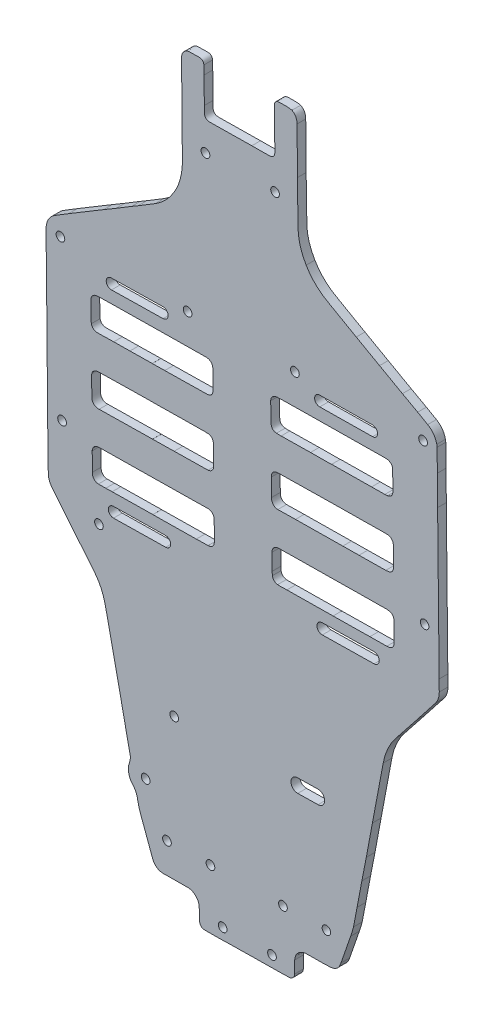
SolidWorks part; units mm, degrees
ref_plane "Front Plane" through (0, 0, 0) normal (0, 0, 1) x (1, 0, 0)
ref_plane "Top Plane" through (0, 0, 0) normal (0, 1, 0) x (1, 0, 0)
ref_plane "Right Plane" through (0, 0, 0) normal (1, 0, 0) x (0, 0, -1)
sketch "Model" plane through (0, 0, 0) normal (0, 0, 1) x (1, 0, 0)
  line L0 (139.9641, 90.6918) -> (146.963, 90.8153) construction
  line L1 (139.9232, 93.0053) -> (146.9221, 93.1288)
  line L2 (140.0049, 88.3782) -> (147.0038, 88.5017)
  line L3 (94.9061, 51.7023) -> (109.9047, 51.9074) construction
  line L4 (109.9047, 51.9074) -> (134.9023, 52.2492) construction
  line L5 (134.9023, 52.2492) -> (149.8915, 52.4542) construction
  line L6 (114.1169, 35.4643) -> (131.1154, 35.6885) construction
  line L7 (76.453, 140.5556) -> (94.4506, 140.8513) construction
  line L8 (76.4243, 142.3054) -> (94.4219, 142.6011)
  line L9 (76.4818, 138.8059) -> (94.4794, 139.1015)
  line L10 (148.4433, 141.7382) -> (166.2947, 142.0315) construction
  line L11 (148.4135, 143.553) -> (166.2649, 143.8463)
  line L12 (148.4731, 139.9235) -> (166.3245, 140.2167)
  line L13 (94.4506, 140.8513) -> (148.4433, 141.7382) construction
  line L14 (58.7447, 159.0469) -> (183.7333, 160.7314) construction
  line L15 (108.1802, 263.6677) -> (132.1775, 264.0236) construction
  line L16 (102.0425, 213.2376) -> (139.0247, 213.7508) construction
  line L17 (58.1737, 213.7002) -> (183.2096, 215.3156) construction
  line L18 (75.7367, 208.357) -> (93.54, 208.6867) construction
  line L19 (75.704, 210.1252) -> (93.5072, 210.4548)
  line L20 (75.7695, 206.5889) -> (93.5727, 206.9185)
  line L21 (147.5691, 209.3184) -> (165.7766, 209.5363) construction
  line L22 (147.5481, 211.0696) -> (165.7556, 211.2876)
  line L23 (147.5901, 207.5672) -> (165.7975, 207.7851)
  circle A0 centre (97.4157, 90.0652) radius 1.5
  circle A1 centre (139.9641, 90.6918) radius 2.3263 construction
  circle A2 centre (146.963, 90.8153) radius 2.2283 construction
  arc A3 (139.9232, 93.0053) -> (140.0049, 88.3782) centre (139.9641, 90.6918) ccw
  arc A4 (147.0038, 88.5017) -> (146.9221, 93.1288) centre (146.963, 90.8153) ccw
  circle A5 centre (87.5642, 66.5167) radius 1.5
  circle A6 centre (94.9061, 51.7023) radius 1.5
  circle A7 centre (109.9047, 51.9074) radius 1.5
  circle A8 centre (134.9023, 52.2492) radius 1.5
  circle A9 centre (149.8915, 52.4542) radius 1.4685
  circle A10 centre (114.1169, 35.4643) radius 1.5
  circle A11 centre (131.1154, 35.6885) radius 1.5
  circle A12 centre (71.4472, 134.4899) radius 1.5
  circle A13 centre (76.453, 140.5556) radius 1.8069 construction
  circle A14 centre (94.4506, 140.8513) radius 1.8089 construction
  arc A15 (76.4243, 142.3054) -> (76.4818, 138.8059) centre (76.453, 140.5556) ccw
  arc A16 (94.4794, 139.1015) -> (94.4219, 142.6011) centre (94.4506, 140.8513) ccw
  circle A17 centre (148.4433, 141.7382) radius 1.8246 construction
  circle A18 centre (166.2947, 142.0315) radius 1.7485 construction
  arc A19 (148.4135, 143.553) -> (148.4731, 139.9235) centre (148.4433, 141.7382) ccw
  arc A20 (166.3245, 140.2167) -> (166.2649, 143.8463) centre (166.2947, 142.0315) ccw
  circle A21 centre (58.7447, 159.0469) radius 1.5
  circle A22 centre (183.7333, 160.7314) radius 1.4757
  circle A23 centre (58.1737, 213.7002) radius 1.5
  circle A24 centre (183.2096, 215.3156) radius 1.5
  circle A25 centre (139.0247, 213.7508) radius 1.5
  circle A26 centre (102.0425, 213.2376) radius 1.5
  circle A27 centre (75.7367, 208.357) radius 1.7708 construction
  circle A28 centre (93.54, 208.6867) radius 1.749 construction
  circle A29 centre (147.5691, 209.3184) radius 1.7119 construction
  circle A30 centre (165.7766, 209.5363) radius 1.6093 construction
  circle A31 centre (108.1802, 263.6677) radius 1.5072
  circle A32 centre (132.1775, 264.0236) radius 1.5
  arc A33 (75.704, 210.1252) -> (75.7695, 206.5889) centre (75.7367, 208.357) ccw
  arc A34 (93.5727, 206.9185) -> (93.5072, 210.4548) centre (93.54, 208.6867) ccw
  arc A35 (147.5481, 211.0696) -> (147.5901, 207.5672) centre (147.5691, 209.3184) ccw
  arc A36 (165.7975, 207.7851) -> (165.7556, 211.2876) centre (165.7766, 209.5363) ccw
  spline S4 degree 3 poles (142.9003, 247.5443) (141.069, 250.6252) (140.1466, 253.9475) (140.0922, 257.5145) (140.0173, 262.4184) (139.9676, 267.3227) (139.9071, 272.2268) knots 130 130 130 130 131 131 131 132 132 132 132
  spline S5 degree 3 poles (160.1719, 234.7234) (157.5712, 236.1953) (154.9628, 237.6544) (152.3806, 239.1582) (151.1155, 239.8951) (149.8109, 240.5609) (148.6004, 241.3999) (146.2423, 243.0343) (144.3647, 245.0806) (142.9003, 247.5443) knots 127 127 127 127 128 128 128 129 129 129 130 130 130 130
  spline S6 degree 3 poles (168.201, 230.1941) (165.5225, 231.7001) (162.8461, 233.2099) (160.1719, 234.7234) knots 126 126 126 126 127 127 127 127
  spline S7 degree 3 poles (176.096, 225.7716) (173.4611, 227.24) (170.8303, 228.7158) (168.201, 230.1941) knots 125 125 125 125 126 126 126 126
  spline S8 degree 3 poles (181.3519, 222.8702) (179.6039, 223.8445) (177.8441, 224.7975) (176.096, 225.7716) knots 124 124 124 124 125 125 125 125
  spline S9 degree 3 poles (184.8034, 220.8988) (183.6645, 221.5754) (182.5092, 222.2252) (181.3519, 222.8702) knots 123 123 123 123 124 124 124 124
  spline S10 degree 3 poles (187.9322, 216.5733) (187.501, 218.4547) (186.4656, 219.9113) (184.8034, 220.8988) knots 122 122 122 122 123 123 123 123
  spline S11 degree 3 poles (188.0372, 215.738) (188.0326, 216.0172) (187.9946, 216.3009) (187.9322, 216.5733) knots 121 121 121 121 122 122 122 122
  spline S12 degree 3 poles (188.1451, 208.0456) (188.12, 210.6099) (188.0795, 213.174) (188.0372, 215.738) knots 120 120 120 120 121 121 121 121
  spline S13 degree 3 poles (188.2239, 197.8176) (188.1913, 201.2269) (188.1784, 204.6363) (188.1451, 208.0456) knots 119 119 119 119 120 120 120 120
  spline S14 degree 3 poles (188.7556, 146.9197) (188.7042, 151.2883) (188.6478, 155.6567) (188.6013, 160.0253) (188.5512, 164.7317) (188.51, 169.4381) (188.4649, 174.1445) (188.4403, 176.709) (188.417, 179.2735) (188.3905, 181.8379) (188.3354, 187.1645) (188.2748, 192.491) (188.2239, 197.8176) knots 115 115 115 115 116 116 116 117 117 117 118 118 118 119 119 119 119
  spline S15 degree 3 poles (188.7942, 143.0303) (188.7997, 144.3267) (188.7708, 145.6233) (188.7556, 146.9197) knots 114 114 114 114 115 115 115 115
  spline S16 degree 3 poles (187.397, 138.9533) (188.3437, 140.1543) (188.7878, 141.5192) (188.7942, 143.0303) knots 113 113 113 113 114 114 114 114
  spline S17 degree 3 poles (180.8225, 130.5686) (183.0204, 133.3585) (185.1982, 136.1642) (187.397, 138.9533) knots 112 112 112 112 113 113 113 113
  spline S18 degree 3 poles (173.8887, 121.8183) (176.2164, 124.7219) (178.5195, 127.6453) (180.8225, 130.5686) knots 111 111 111 111 112 112 112 112
  spline S19 degree 3 poles (169.4641, 112.1583) (170.1296, 115.7502) (171.6011, 118.9649) (173.8887, 121.8183) knots 110 110 110 110 111 111 111 111
  spline S20 degree 3 poles (165.7408, 92.3847) (166.3738, 95.7638) (167.0172, 99.1409) (167.6539, 102.5194) (168.2593, 105.732) (168.8685, 108.9439) (169.4641, 112.1583) knots 108 108 108 108 109 109 109 110 110 110 110
  spline S21 degree 3 poles (163.6335, 81.0824) (164.3484, 84.8475) (165.0352, 88.6179) (165.7408, 92.3847) knots 107 107 107 107 108 108 108 108
  spline S22 degree 3 poles (162.1011, 73.284) (162.6007, 75.8856) (163.1393, 78.4798) (163.6335, 81.0824) knots 106 106 106 106 107 107 107 107
  spline S23 degree 3 poles (160.4605, 64.5599) (161.0078, 67.4678) (161.5431, 70.3781) (162.1011, 73.284) knots 105 105 105 105 106 106 106 106
  spline S24 degree 3 poles (159.2194, 58.0847) (159.6825, 60.2325) (160.0539, 62.4) (160.4605, 64.5599) knots 104 104 104 104 105 105 105 105
  spline S25 degree 3 poles (158.2451, 54.8489) (158.6086, 55.915) (158.9827, 56.987) (159.2194, 58.0847) knots 103 103 103 103 104 104 104 104
  spline S26 degree 3 poles (154.9028, 45.1834) (156.0192, 48.4045) (157.1447, 51.6224) (158.2451, 54.8489) knots 102 102 102 102 103 103 103 103
  spline S27 degree 3 poles (151.3871, 42.1194) (153.0147, 42.2825) (154.1498, 43.154) (154.7271, 44.7075) (154.786, 44.866) (154.8475, 45.0237) (154.9028, 45.1834) knots 100 100 100 100 101 101 101 102 102 102 102
  spline S28 degree 3 poles (148.1754, 42.0036) (149.2467, 42.0186) (150.3233, 42.0128) (151.3871, 42.1194) knots 99 99 99 99 100 100 100 100
  spline S29 degree 3 poles (143.0988, 41.9752) (144.791, 41.972) (146.4834, 41.9799) (148.1754, 42.0036) knots 98 98 98 98 99 99 99 99
  spline S30 degree 3 poles (140.5049, 41.0881) (141.2625, 41.6639) (142.1265, 41.9771) (143.0988, 41.9752) knots 97 97 97 97 98 98 98 98
  spline S31 degree 3 poles (138.9467, 38.1109) (139.035, 39.3178) (139.5292, 40.3467) (140.5049, 41.0881) knots 96 96 96 96 97 97 97 97
  spline S32 degree 3 poles (138.9119, 33.8855) (138.9418, 34.6453) (138.937, 35.4066) (138.9411, 36.1672) (138.9446, 36.8153) (138.8995, 37.4663) (138.9467, 38.1109) knots 94 94 94 94 95 95 95 96 96 96 96
  spline S33 degree 3 poles (138.0031, 32.2575) (138.6028, 32.6406) (138.8849, 33.1995) (138.9119, 33.8855) knots 93 93 93 93 94 94 94 94
  spline S34 degree 3 poles (136.958, 31.9779) (137.3316, 31.9881) (137.6792, 32.0506) (138.0031, 32.2575) knots 92 92 92 92 93 93 93 93
  spline S35 degree 3 poles (133.7475, 31.877) (134.8179, 31.89) (135.8877, 31.9487) (136.958, 31.9779) knots 91 91 91 91 92 92 92 92
  spline S36 degree 3 poles (125.2044, 31.7805) (125.6548, 31.8038) (126.1062, 31.8173) (126.5572, 31.8211) (128.954, 31.8409) (131.3509, 31.8479) (133.7475, 31.877) knots 89 89 89 89 90 90 90 91 91 91 91
  spline S37 degree 3 poles (117.3384, 31.6588) (119.9605, 31.6911) (122.5837, 31.6452) (125.2044, 31.7805) knots 88 88 88 88 89 89 89 89
  spline S38 degree 3 poles (112.0108, 31.5401) (113.7869, 31.5689) (115.5623, 31.637) (117.3384, 31.6588) knots 87 87 87 87 88 88 88 88
  spline S39 degree 3 poles (108.0341, 31.5229) (109.3597, 31.5233) (110.6855, 31.5186) (112.0108, 31.5401) knots 86 86 86 86 87 87 87 87
  spline S40 degree 3 poles (106.1411, 33.3488) (106.1519, 33.0753) (106.2148, 32.7866) (106.3265, 32.5375) (106.6521, 31.8113) (107.2669, 31.5226) (108.0341, 31.5229) knots 84 84 84 84 85 85 85 86 86 86 86
  spline S41 degree 3 poles (106.0416, 36.9829) (106.0723, 35.7714) (106.0932, 34.5595) (106.1411, 33.3488) knots 83 83 83 83 84 84 84 84
  spline S42 degree 3 poles (102.9837, 41.2297) (104.6722, 40.7902) (105.888, 39.3158) (106.0244, 37.5745) (106.0398, 37.378) (106.0366, 37.1801) (106.0416, 36.9829) knots 81 81 81 81 82 82 82 83 83 83 83
  spline S43 degree 3 poles (93.7725, 41.2707) (94.1106, 41.2845) (94.4492, 41.2927) (94.7875, 41.2948) (97.1846, 41.3097) (99.5817, 41.3264) (101.9787, 41.3311) (102.3143, 41.3318) (102.6614, 41.3137) (102.9837, 41.2297) knots 78 78 78 78 79 79 79 80 80 80 81 81 81 81
  spline S44 degree 3 poles (89.9866, 43.8239) (90.5775, 42.2091) (92.0697, 41.2011) (93.7725, 41.2707) knots 77 77 77 77 78 78 78 78
  spline S45 degree 3 poles (88.4375, 48.027) (88.9524, 46.6254) (89.4736, 45.2261) (89.9866, 43.8239) knots 76 76 76 76 77 77 77 77
  spline S46 degree 3 poles (87.0134, 51.9152) (87.4931, 50.621) (87.9614, 49.3226) (88.4375, 48.027) knots 75 75 75 75 76 76 76 76
  spline S47 degree 3 poles (85.9067, 54.8403) (86.278, 53.8661) (86.6512, 52.8927) (87.0134, 51.9152) knots 74 74 74 74 75 75 75 75
  spline S48 degree 3 poles (84.6614, 59.5748) (84.7304, 59.2438) (84.7994, 58.9128) (84.8655, 58.5811) (85.1191, 57.3082) (85.4437, 56.0552) (85.9067, 54.8403) knots 72 72 72 72 73 73 73 74 74 74 74
  spline S49 degree 3 poles (83.2196, 62.3994) (83.9638, 61.5882) (84.4377, 60.6472) (84.6614, 59.5748) knots 71 71 71 71 72 72 72 72
  spline S50 degree 3 poles (81.6144, 66.8067) (81.5485, 65.1218) (82.0777, 63.6441) (83.2196, 62.3994) knots 70 70 70 70 71 71 71 71
  spline S51 degree 3 poles (82.0709, 68.8609) (81.9624, 68.4816) (81.8382, 68.106) (81.7495, 67.7222) (81.6802, 67.4223) (81.6264, 67.1135) (81.6144, 66.8067) knots 68 68 68 68 69 69 69 70 70 70 70
  spline S52 degree 3 poles (82.1755, 71.1976) (82.3609, 70.4025) (82.2914, 69.6314) (82.0709, 68.8609) knots 67 67 67 67 68 68 68 68
  spline S53 degree 3 poles (81.4258, 74.6659) (81.667, 73.508) (81.907, 72.3494) (82.1755, 71.1976) knots 66 66 66 66 67 67 67 67
  spline S54 degree 3 poles (79.5901, 83.5201) (80.2074, 80.5698) (80.8111, 77.6167) (81.4258, 74.6659) knots 65 65 65 65 66 66 66 66
  spline S55 degree 3 poles (77.5825, 93.0283) (78.2562, 89.8598) (78.9267, 86.6907) (79.5901, 83.5201) knots 64 64 64 64 65 65 65 65
  spline S56 degree 3 poles (70.0796, 119.2301) (71.9127, 116.8747) (73.0514, 114.1948) (73.6788, 111.2903) (74.2557, 108.6194) (74.821, 105.946) (75.3922, 103.2738) (76.1222, 99.8586) (76.8561, 96.4442) (77.5825, 93.0283) knots 61 61 61 61 62 62 62 63 63 63 64 64 64 64
  spline S57 degree 3 poles (67.1429, 122.8361) (68.1272, 121.6384) (69.1278, 120.4531) (70.0796, 119.2301) knots 60 60 60 60 61 61 61 61
  spline S58 degree 3 poles (64.1797, 126.42) (65.1631, 125.2219) (66.1586, 124.0336) (67.1429, 122.8361) knots 59 59 59 59 60 60 60 60
  spline S59 degree 3 poles (54.8726, 137.9207) (55.1048, 137.5362) (55.3727, 137.1692) (55.6572, 136.8211) (58.4939, 133.3506) (61.336, 129.8847) (64.1797, 126.42) knots 57 57 57 57 58 58 58 59 59 59 59
  spline S60 degree 3 poles (53.7241, 162.6042) (53.741, 160.716) (53.7623, 158.828) (53.7809, 156.9399) (53.7982, 155.1928) (53.8135, 153.4458) (53.8318, 151.6988) (53.8544, 149.5289) (53.8734, 147.3589) (53.905, 145.1891) (53.9268, 143.6959) (53.9713, 142.2031) (53.9979, 140.71) (54.016, 139.6928) (54.3559, 138.7761) (54.8726, 137.9207) knots 52 52 52 52 53 53 53 54 54 54 55 55 55 56 56 56 57 57 57 57
  spline S61 degree 3 poles (53.5194, 185.6015) (53.5715, 180.5287) (53.6138, 175.4559) (53.659, 170.383) (53.6821, 167.7901) (53.7009, 165.1971) (53.7241, 162.6042) knots 50 50 50 50 51 51 51 52 52 52 52
  spline S62 degree 3 poles (60.9788, 221.9618) (59.503, 221.0789) (58.0378, 220.1783) (56.5642, 219.2916) (54.3168, 217.9393) (53.2091, 215.9422) (53.2169, 213.3347) (53.2229, 211.3055) (53.274, 209.2765) (53.2945, 207.2473) (53.3236, 204.3726) (53.3374, 201.4976) (53.368, 198.6229) (53.4143, 194.2824) (53.4748, 189.942) (53.5194, 185.6015) knots 45 45 45 45 46 46 46 47 47 47 48 48 48 49 49 49 50 50 50 50
  spline S63 degree 3 poles (73.0871, 229.2281) (71.3705, 228.1995) (69.6694, 227.1452) (67.9531, 226.1162) (65.6323, 224.7249) (63.3009, 223.351) (60.9788, 221.9618) knots 43 43 43 43 44 44 44 45 45 45 45
  spline S64 degree 3 poles (77.3857, 231.7625) (75.9595, 230.9067) (74.5139, 230.083) (73.0871, 229.2281) knots 42 42 42 42 43 43 43 43
  spline S65 degree 3 poles (82.7345, 235.0097) (80.9495, 233.9307) (79.1742, 232.8357) (77.3857, 231.7625) knots 41 41 41 41 42 42 42 42
  spline S66 degree 3 poles (84.9208, 236.2974) (84.1967, 235.8604) (83.4582, 235.4473) (82.7345, 235.0097) knots 40 40 40 40 41 41 41 41
  spline S67 degree 3 poles (90.8491, 239.8959) (88.8872, 238.6738) (86.9001, 237.4917) (84.9208, 236.2974) knots 39 39 39 39 40 40 40 40
  spline S68 degree 3 poles (97.434, 246.6892) (95.7903, 243.8891) (93.6043, 241.6121) (90.8491, 239.8959) knots 38 38 38 38 39 39 39 39
  spline S69 degree 3 poles (100.2156, 256.2477) (100.0817, 252.8378) (99.1677, 249.6426) (97.434, 246.6892) knots 37 37 37 37 38 38 38 38
  spline S70 degree 3 poles (100.2038, 260.644) (100.2144, 259.1785) (100.2731, 257.7108) (100.2156, 256.2477) knots 36 36 36 36 37 37 37 37
  spline S71 degree 3 poles (100.1716, 262.8417) (100.182, 262.1091) (100.1985, 261.3766) (100.2038, 260.644) knots 35 35 35 35 36 36 36 36
  spline S72 degree 3 poles (100.0864, 269.0113) (100.1084, 266.9547) (100.1423, 264.8982) (100.1716, 262.8417) knots 34 34 34 34 35 35 35 35
  spline S73 degree 3 poles (100.0429, 278.3956) (100.0566, 276.5639) (100.0643, 274.7321) (100.0724, 272.9003) (100.0782, 271.6039) (100.0725, 270.3075) (100.0864, 269.0113) knots 32 32 32 32 33 33 33 34 34 34 34
  spline S74 degree 3 poles (100.0033, 280.931) (100.0153, 280.0859) (100.0366, 279.2408) (100.0429, 278.3956) knots 31 31 31 31 32 32 32 32
  spline S75 degree 3 poles (99.9956, 282.1143) (100.0017, 281.7199) (99.9978, 281.3254) (100.0033, 280.931) knots 30 30 30 30 31 31 31 31
  spline S76 degree 3 poles (99.9531, 284.6488) (99.9567, 283.8039) (99.9827, 282.9591) (99.9956, 282.1143) knots 29 29 29 29 30 30 30 30
  spline S77 degree 3 poles (99.9671, 288.3684) (99.9332, 287.1293) (99.9479, 285.8887) (99.9531, 284.6488) knots 28 28 28 28 29 29 29 29
  spline S78 degree 3 poles (107.6183, 289.6636) (107.5702, 290.652) (106.9465, 291.2103) (105.9719, 291.1885) (104.9293, 291.1652) (103.8859, 291.1018) (102.8444, 291.1253) (101.5538, 291.1543) (100.0133, 290.0568) (99.9671, 288.3684) knots 25 25 25 25 26 26 26 27 27 27 28 28 28 28
  spline S79 degree 3 poles (107.6931, 286.7053) (107.6803, 287.6916) (107.6663, 288.6786) (107.6183, 289.6636) knots 24 24 24 24 25 25 25 25
  spline S80 degree 3 poles (107.7974, 277.6611) (107.7645, 280.6759) (107.7322, 283.6906) (107.6931, 286.7053) knots 23 23 23 23 24 24 24 24
  spline S81 degree 3 poles (124.1692, 273.8325) (121.97, 273.7978) (119.771, 273.7549) (117.5718, 273.7198) (117.0925, 273.7122) (116.6128, 273.7325) (116.1335, 273.7257) (114.019, 273.696) (111.9046, 273.6445) (109.79, 273.6342) (108.5192, 273.6281) (107.8463, 274.2989) (107.8104, 275.5473) (107.7902, 276.2514) (107.805, 276.9565) (107.7974, 277.6611) knots 18 18 18 18 19 19 19 20 20 20 21 21 21 22 22 22 23 23 23 23
  spline S82 degree 3 poles (132.0907, 275.5877) (132.0284, 274.6207) (131.4786, 274.0383) (130.5125, 273.9085) (130.3732, 273.8898) (130.2315, 273.8842) (130.0908, 273.8822) (128.6246, 273.8616) (127.1584, 273.8404) (125.6921, 273.8251) (125.1845, 273.8198) (124.6766, 273.8405) (124.1692, 273.8325) knots 14 14 14 14 15 15 15 16 16 16 17 17 17 18 18 18 18
  spline S83 degree 3 poles (132.0514, 282.6886) (132.0648, 280.5752) (132.0825, 278.4619) (132.0973, 276.3485) (132.0991, 276.0949) (132.107, 275.8404) (132.0907, 275.5877) knots 12 12 12 12 13 13 13 14 14 14 14
  spline S84 degree 3 poles (132.0259, 287.5917) (132.0394, 285.9574) (132.0411, 284.323) (132.0514, 282.6886) knots 11 11 11 11 12 12 12 12
  spline S85 degree 3 poles (132.0193, 290.2069) (131.9609, 289.7629) (131.9705, 289.3082) (131.9731, 288.8584) (131.9755, 288.4361) (132.0225, 288.0141) (132.0259, 287.5917) knots 9 9 9 9 10 10 10 11 11 11 11
  spline S86 degree 3 poles (137.9793, 291.3136) (137.5876, 291.4547) (137.1572, 291.5357) (136.7409, 291.5516) (135.8397, 291.586) (134.9362, 291.5677) (134.0339, 291.5561) (133.7535, 291.5525) (133.4688, 291.5249) (133.1948, 291.4668) (132.4958, 291.3188) (132.1139, 290.9262) (132.0193, 290.2069) knots 5 5 5 5 6 6 6 7 7 7 8 8 8 9 9 9 9
  spline S87 degree 3 poles (139.7534, 288.1227) (139.745, 288.5417) (139.7095, 288.9755) (139.5906, 289.3739) (139.3329, 290.2373) (138.8817, 290.9887) (137.9793, 291.3136) knots 3 3 3 3 4 4 4 5 5 5 5
  spline S88 degree 3 poles (139.9245, 272.227) (139.8884, 275.8064) (139.8527, 279.3858) (139.816, 282.9652) (139.7984, 284.6844) (139.7879, 286.4038) (139.7534, 288.1227) knots 1 1 1 1 2 2 2 3 3 3 3
  spline S89 degree 3 poles (139.9071, 272.2268) (139.9129, 272.2269) (139.9187, 272.2269) (139.9245, 272.227) knots 0 0 0 0 1 1 1 1
  spline S90 degree 3 poles (139.9245, 272.227) (139.9187, 272.2269) (139.9129, 272.2269) (139.9071, 272.2268) knots 131 131 131 131 132 132 132 132
  spline S91 degree 3 poles (139.7534, 288.1227) (139.7879, 286.4038) (139.7984, 284.6844) (139.816, 282.9652) (139.8527, 279.3858) (139.8884, 275.8064) (139.9245, 272.227) knots 129 129 129 129 130 130 130 131 131 131 131
  spline S92 degree 3 poles (137.9793, 291.3136) (138.8817, 290.9887) (139.3329, 290.2373) (139.5906, 289.3739) (139.7095, 288.9755) (139.745, 288.5417) (139.7534, 288.1227) knots 127 127 127 127 128 128 128 129 129 129 129
  spline S93 degree 3 poles (132.0193, 290.2069) (132.1139, 290.9262) (132.4958, 291.3188) (133.1948, 291.4668) (133.4688, 291.5249) (133.7535, 291.5525) (134.0339, 291.5561) (134.9362, 291.5677) (135.8397, 291.586) (136.7409, 291.5516) (137.1572, 291.5357) (137.5876, 291.4547) (137.9793, 291.3136) knots 123 123 123 123 124 124 124 125 125 125 126 126 126 127 127 127 127
  spline S94 degree 3 poles (132.0259, 287.5917) (132.0225, 288.0141) (131.9755, 288.4361) (131.9731, 288.8584) (131.9705, 289.3082) (131.9609, 289.7629) (132.0193, 290.2069) knots 121 121 121 121 122 122 122 123 123 123 123
  spline S95 degree 3 poles (132.0514, 282.6886) (132.0411, 284.323) (132.0394, 285.9574) (132.0259, 287.5917) knots 120 120 120 120 121 121 121 121
  spline S96 degree 3 poles (132.0907, 275.5877) (132.107, 275.8404) (132.0991, 276.0949) (132.0973, 276.3485) (132.0825, 278.4619) (132.0648, 280.5752) (132.0514, 282.6886) knots 118 118 118 118 119 119 119 120 120 120 120
  spline S97 degree 3 poles (124.1692, 273.8325) (124.6766, 273.8405) (125.1845, 273.8198) (125.6921, 273.8251) (127.1584, 273.8404) (128.6246, 273.8616) (130.0908, 273.8822) (130.2315, 273.8842) (130.3732, 273.8898) (130.5125, 273.9085) (131.4786, 274.0383) (132.0284, 274.6207) (132.0907, 275.5877) knots 114 114 114 114 115 115 115 116 116 116 117 117 117 118 118 118 118
  spline S98 degree 3 poles (107.7974, 277.6611) (107.805, 276.9565) (107.7902, 276.2514) (107.8104, 275.5473) (107.8463, 274.2989) (108.5192, 273.6281) (109.79, 273.6342) (111.9046, 273.6445) (114.019, 273.696) (116.1335, 273.7257) (116.6128, 273.7325) (117.0925, 273.7122) (117.5718, 273.7198) (119.771, 273.7549) (121.97, 273.7978) (124.1692, 273.8325) knots 109 109 109 109 110 110 110 111 111 111 112 112 112 113 113 113 114 114 114 114
  spline S99 degree 3 poles (107.6931, 286.7053) (107.7322, 283.6906) (107.7645, 280.6759) (107.7974, 277.6611) knots 108 108 108 108 109 109 109 109
  spline S100 degree 3 poles (107.6183, 289.6636) (107.6663, 288.6786) (107.6803, 287.6916) (107.6931, 286.7053) knots 107 107 107 107 108 108 108 108
  spline S101 degree 3 poles (99.9671, 288.3684) (100.0133, 290.0568) (101.5538, 291.1543) (102.8444, 291.1253) (103.8859, 291.1018) (104.9293, 291.1652) (105.9719, 291.1885) (106.9465, 291.2103) (107.5702, 290.652) (107.6183, 289.6636) knots 104 104 104 104 105 105 105 106 106 106 107 107 107 107
  spline S102 degree 3 poles (99.9531, 284.6488) (99.9479, 285.8887) (99.9332, 287.1293) (99.9671, 288.3684) knots 103 103 103 103 104 104 104 104
  spline S103 degree 3 poles (99.9956, 282.1143) (99.9827, 282.9591) (99.9567, 283.8039) (99.9531, 284.6488) knots 102 102 102 102 103 103 103 103
  spline S104 degree 3 poles (100.0033, 280.931) (99.9978, 281.3254) (100.0017, 281.7199) (99.9956, 282.1143) knots 101 101 101 101 102 102 102 102
  spline S105 degree 3 poles (100.0429, 278.3956) (100.0366, 279.2408) (100.0153, 280.0859) (100.0033, 280.931) knots 100 100 100 100 101 101 101 101
  spline S106 degree 3 poles (100.0864, 269.0113) (100.0725, 270.3075) (100.0782, 271.6039) (100.0724, 272.9003) (100.0643, 274.7321) (100.0566, 276.5639) (100.0429, 278.3956) knots 98 98 98 98 99 99 99 100 100 100 100
  spline S107 degree 3 poles (100.1716, 262.8417) (100.1423, 264.8982) (100.1084, 266.9547) (100.0864, 269.0113) knots 97 97 97 97 98 98 98 98
  spline S108 degree 3 poles (100.2038, 260.644) (100.1985, 261.3766) (100.182, 262.1091) (100.1716, 262.8417) knots 96 96 96 96 97 97 97 97
  spline S109 degree 3 poles (100.2156, 256.2477) (100.2731, 257.7108) (100.2144, 259.1785) (100.2038, 260.644) knots 95 95 95 95 96 96 96 96
  spline S110 degree 3 poles (97.434, 246.6892) (99.1677, 249.6426) (100.0817, 252.8378) (100.2156, 256.2477) knots 94 94 94 94 95 95 95 95
  spline S111 degree 3 poles (90.8491, 239.8959) (93.6043, 241.6121) (95.7903, 243.8891) (97.434, 246.6892) knots 93 93 93 93 94 94 94 94
  spline S112 degree 3 poles (84.9208, 236.2974) (86.9001, 237.4917) (88.8872, 238.6738) (90.8491, 239.8959) knots 92 92 92 92 93 93 93 93
  spline S113 degree 3 poles (82.7345, 235.0097) (83.4582, 235.4473) (84.1967, 235.8604) (84.9208, 236.2974) knots 91 91 91 91 92 92 92 92
  spline S114 degree 3 poles (77.3857, 231.7625) (79.1742, 232.8357) (80.9495, 233.9307) (82.7345, 235.0097) knots 90 90 90 90 91 91 91 91
  spline S115 degree 3 poles (73.0871, 229.2281) (74.5139, 230.083) (75.9595, 230.9067) (77.3857, 231.7625) knots 89 89 89 89 90 90 90 90
  spline S116 degree 3 poles (60.9788, 221.9618) (63.3009, 223.351) (65.6323, 224.7249) (67.9531, 226.1162) (69.6694, 227.1452) (71.3705, 228.1995) (73.0871, 229.2281) knots 87 87 87 87 88 88 88 89 89 89 89
  spline S117 degree 3 poles (53.5194, 185.6015) (53.4748, 189.942) (53.4143, 194.2824) (53.368, 198.6229) (53.3374, 201.4976) (53.3236, 204.3726) (53.2945, 207.2473) (53.274, 209.2765) (53.2229, 211.3055) (53.2169, 213.3347) (53.2091, 215.9422) (54.3168, 217.9393) (56.5642, 219.2916) (58.0378, 220.1783) (59.503, 221.0789) (60.9788, 221.9618) knots 82 82 82 82 83 83 83 84 84 84 85 85 85 86 86 86 87 87 87 87
  spline S118 degree 3 poles (53.7241, 162.6042) (53.7009, 165.1971) (53.6821, 167.7901) (53.659, 170.383) (53.6138, 175.4559) (53.5715, 180.5287) (53.5194, 185.6015) knots 80 80 80 80 81 81 81 82 82 82 82
  spline S119 degree 3 poles (54.8726, 137.9207) (54.3559, 138.7761) (54.016, 139.6928) (53.9979, 140.71) (53.9713, 142.2031) (53.9268, 143.6959) (53.905, 145.1891) (53.8734, 147.3589) (53.8544, 149.5289) (53.8318, 151.6988) (53.8135, 153.4458) (53.7982, 155.1928) (53.7809, 156.9399) (53.7623, 158.828) (53.741, 160.716) (53.7241, 162.6042) knots 75 75 75 75 76 76 76 77 77 77 78 78 78 79 79 79 80 80 80 80
  spline S120 degree 3 poles (64.1797, 126.42) (61.336, 129.8847) (58.4939, 133.3506) (55.6572, 136.8211) (55.3727, 137.1692) (55.1048, 137.5362) (54.8726, 137.9207) knots 73 73 73 73 74 74 74 75 75 75 75
  spline S121 degree 3 poles (67.1429, 122.8361) (66.1586, 124.0336) (65.1631, 125.2219) (64.1797, 126.42) knots 72 72 72 72 73 73 73 73
  spline S122 degree 3 poles (70.0796, 119.2301) (69.1278, 120.4531) (68.1272, 121.6384) (67.1429, 122.8361) knots 71 71 71 71 72 72 72 72
  spline S123 degree 3 poles (77.5825, 93.0283) (76.8561, 96.4442) (76.1222, 99.8586) (75.3922, 103.2738) (74.821, 105.946) (74.2557, 108.6194) (73.6788, 111.2903) (73.0514, 114.1948) (71.9127, 116.8747) (70.0796, 119.2301) knots 68 68 68 68 69 69 69 70 70 70 71 71 71 71
  spline S124 degree 3 poles (79.5901, 83.5201) (78.9267, 86.6907) (78.2562, 89.8598) (77.5825, 93.0283) knots 67 67 67 67 68 68 68 68
  spline S125 degree 3 poles (81.4258, 74.6659) (80.8111, 77.6167) (80.2074, 80.5698) (79.5901, 83.5201) knots 66 66 66 66 67 67 67 67
  spline S126 degree 3 poles (82.1755, 71.1976) (81.907, 72.3494) (81.667, 73.508) (81.4258, 74.6659) knots 65 65 65 65 66 66 66 66
  spline S127 degree 3 poles (82.0709, 68.8609) (82.2914, 69.6314) (82.3609, 70.4025) (82.1755, 71.1976) knots 64 64 64 64 65 65 65 65
  spline S128 degree 3 poles (81.6144, 66.8067) (81.6264, 67.1135) (81.6802, 67.4223) (81.7495, 67.7222) (81.8382, 68.106) (81.9624, 68.4816) (82.0709, 68.8609) knots 62 62 62 62 63 63 63 64 64 64 64
  spline S129 degree 3 poles (83.2196, 62.3994) (82.0777, 63.6441) (81.5485, 65.1218) (81.6144, 66.8067) knots 61 61 61 61 62 62 62 62
  spline S130 degree 3 poles (84.6614, 59.5748) (84.4377, 60.6472) (83.9638, 61.5882) (83.2196, 62.3994) knots 60 60 60 60 61 61 61 61
  spline S131 degree 3 poles (85.9067, 54.8403) (85.4437, 56.0552) (85.1191, 57.3082) (84.8655, 58.5811) (84.7994, 58.9128) (84.7304, 59.2438) (84.6614, 59.5748) knots 58 58 58 58 59 59 59 60 60 60 60
  spline S132 degree 3 poles (87.0134, 51.9152) (86.6512, 52.8927) (86.278, 53.8661) (85.9067, 54.8403) knots 57 57 57 57 58 58 58 58
  spline S133 degree 3 poles (88.4375, 48.027) (87.9614, 49.3226) (87.4931, 50.621) (87.0134, 51.9152) knots 56 56 56 56 57 57 57 57
  spline S134 degree 3 poles (89.9866, 43.8239) (89.4736, 45.2261) (88.9524, 46.6254) (88.4375, 48.027) knots 55 55 55 55 56 56 56 56
  spline S135 degree 3 poles (93.7725, 41.2707) (92.0697, 41.2011) (90.5775, 42.2091) (89.9866, 43.8239) knots 54 54 54 54 55 55 55 55
  spline S136 degree 3 poles (102.9837, 41.2297) (102.6614, 41.3137) (102.3143, 41.3318) (101.9787, 41.3311) (99.5817, 41.3264) (97.1846, 41.3097) (94.7875, 41.2948) (94.4492, 41.2927) (94.1106, 41.2845) (93.7725, 41.2707) knots 51 51 51 51 52 52 52 53 53 53 54 54 54 54
  spline S137 degree 3 poles (106.0416, 36.9829) (106.0366, 37.1801) (106.0398, 37.378) (106.0244, 37.5745) (105.888, 39.3158) (104.6722, 40.7902) (102.9837, 41.2297) knots 49 49 49 49 50 50 50 51 51 51 51
  spline S138 degree 3 poles (106.1411, 33.3488) (106.0932, 34.5595) (106.0723, 35.7714) (106.0416, 36.9829) knots 48 48 48 48 49 49 49 49
  spline S139 degree 3 poles (108.0341, 31.5229) (107.2669, 31.5226) (106.6521, 31.8113) (106.3265, 32.5375) (106.2148, 32.7866) (106.1519, 33.0753) (106.1411, 33.3488) knots 46 46 46 46 47 47 47 48 48 48 48
  spline S140 degree 3 poles (112.0108, 31.5401) (110.6855, 31.5186) (109.3597, 31.5233) (108.0341, 31.5229) knots 45 45 45 45 46 46 46 46
  spline S141 degree 3 poles (117.3384, 31.6588) (115.5623, 31.637) (113.7869, 31.5689) (112.0108, 31.5401) knots 44 44 44 44 45 45 45 45
  spline S142 degree 3 poles (125.2044, 31.7805) (122.5837, 31.6452) (119.9605, 31.6911) (117.3384, 31.6588) knots 43 43 43 43 44 44 44 44
  spline S143 degree 3 poles (133.7475, 31.877) (131.3509, 31.8479) (128.954, 31.8409) (126.5572, 31.8211) (126.1062, 31.8173) (125.6548, 31.8038) (125.2044, 31.7805) knots 41 41 41 41 42 42 42 43 43 43 43
  spline S144 degree 3 poles (136.958, 31.9779) (135.8877, 31.9487) (134.8179, 31.89) (133.7475, 31.877) knots 40 40 40 40 41 41 41 41
  spline S145 degree 3 poles (138.0031, 32.2575) (137.6792, 32.0506) (137.3316, 31.9881) (136.958, 31.9779) knots 39 39 39 39 40 40 40 40
  spline S146 degree 3 poles (138.9119, 33.8855) (138.8849, 33.1995) (138.6028, 32.6406) (138.0031, 32.2575) knots 38 38 38 38 39 39 39 39
  spline S147 degree 3 poles (138.9467, 38.1109) (138.8995, 37.4663) (138.9446, 36.8153) (138.9411, 36.1672) (138.937, 35.4066) (138.9418, 34.6453) (138.9119, 33.8855) knots 36 36 36 36 37 37 37 38 38 38 38
  spline S148 degree 3 poles (140.5049, 41.0881) (139.5292, 40.3467) (139.035, 39.3178) (138.9467, 38.1109) knots 35 35 35 35 36 36 36 36
  spline S149 degree 3 poles (143.0988, 41.9752) (142.1265, 41.9771) (141.2625, 41.6639) (140.5049, 41.0881) knots 34 34 34 34 35 35 35 35
  spline S150 degree 3 poles (148.1754, 42.0036) (146.4834, 41.9799) (144.791, 41.972) (143.0988, 41.9752) knots 33 33 33 33 34 34 34 34
  spline S151 degree 3 poles (151.3871, 42.1194) (150.3233, 42.0128) (149.2467, 42.0186) (148.1754, 42.0036) knots 32 32 32 32 33 33 33 33
  spline S152 degree 3 poles (154.9028, 45.1834) (154.8475, 45.0237) (154.786, 44.866) (154.7271, 44.7075) (154.1498, 43.154) (153.0147, 42.2825) (151.3871, 42.1194) knots 30 30 30 30 31 31 31 32 32 32 32
  spline S153 degree 3 poles (158.2451, 54.8489) (157.1447, 51.6224) (156.0192, 48.4045) (154.9028, 45.1834) knots 29 29 29 29 30 30 30 30
  spline S154 degree 3 poles (159.2194, 58.0847) (158.9827, 56.987) (158.6086, 55.915) (158.2451, 54.8489) knots 28 28 28 28 29 29 29 29
  spline S155 degree 3 poles (160.4605, 64.5599) (160.0539, 62.4) (159.6825, 60.2325) (159.2194, 58.0847) knots 27 27 27 27 28 28 28 28
  spline S156 degree 3 poles (162.1011, 73.284) (161.5431, 70.3781) (161.0078, 67.4678) (160.4605, 64.5599) knots 26 26 26 26 27 27 27 27
  spline S157 degree 3 poles (163.6335, 81.0824) (163.1393, 78.4798) (162.6007, 75.8856) (162.1011, 73.284) knots 25 25 25 25 26 26 26 26
  spline S158 degree 3 poles (165.7408, 92.3847) (165.0352, 88.6179) (164.3484, 84.8475) (163.6335, 81.0824) knots 24 24 24 24 25 25 25 25
  spline S159 degree 3 poles (169.4641, 112.1583) (168.8685, 108.9439) (168.2593, 105.732) (167.6539, 102.5194) (167.0172, 99.1409) (166.3738, 95.7638) (165.7408, 92.3847) knots 22 22 22 22 23 23 23 24 24 24 24
  spline S160 degree 3 poles (173.8887, 121.8183) (171.6011, 118.9649) (170.1296, 115.7502) (169.4641, 112.1583) knots 21 21 21 21 22 22 22 22
  spline S161 degree 3 poles (180.8225, 130.5686) (178.5195, 127.6453) (176.2164, 124.7219) (173.8887, 121.8183) knots 20 20 20 20 21 21 21 21
  spline S162 degree 3 poles (187.397, 138.9533) (185.1982, 136.1642) (183.0204, 133.3585) (180.8225, 130.5686) knots 19 19 19 19 20 20 20 20
  spline S163 degree 3 poles (188.7942, 143.0303) (188.7878, 141.5192) (188.3437, 140.1543) (187.397, 138.9533) knots 18 18 18 18 19 19 19 19
  spline S164 degree 3 poles (188.7556, 146.9197) (188.7708, 145.6233) (188.7997, 144.3267) (188.7942, 143.0303) knots 17 17 17 17 18 18 18 18
  spline S165 degree 3 poles (188.2239, 197.8176) (188.2748, 192.491) (188.3354, 187.1645) (188.3905, 181.8379) (188.417, 179.2735) (188.4403, 176.709) (188.4649, 174.1445) (188.51, 169.4381) (188.5512, 164.7317) (188.6013, 160.0253) (188.6478, 155.6567) (188.7042, 151.2883) (188.7556, 146.9197) knots 13 13 13 13 14 14 14 15 15 15 16 16 16 17 17 17 17
  spline S166 degree 3 poles (188.1451, 208.0456) (188.1784, 204.6363) (188.1913, 201.2269) (188.2239, 197.8176) knots 12 12 12 12 13 13 13 13
  spline S167 degree 3 poles (188.0372, 215.738) (188.0795, 213.174) (188.12, 210.6099) (188.1451, 208.0456) knots 11 11 11 11 12 12 12 12
  spline S168 degree 3 poles (187.9322, 216.5733) (187.9946, 216.3009) (188.0326, 216.0172) (188.0372, 215.738) knots 10 10 10 10 11 11 11 11
  spline S169 degree 3 poles (184.8034, 220.8988) (186.4656, 219.9113) (187.501, 218.4547) (187.9322, 216.5733) knots 9 9 9 9 10 10 10 10
  spline S170 degree 3 poles (181.3519, 222.8702) (182.5092, 222.2252) (183.6645, 221.5754) (184.8034, 220.8988) knots 8 8 8 8 9 9 9 9
  spline S171 degree 3 poles (176.096, 225.7716) (177.8441, 224.7975) (179.6039, 223.8445) (181.3519, 222.8702) knots 7 7 7 7 8 8 8 8
  spline S172 degree 3 poles (168.201, 230.1941) (170.8303, 228.7158) (173.4611, 227.24) (176.096, 225.7716) knots 6 6 6 6 7 7 7 7
  spline S173 degree 3 poles (160.1719, 234.7234) (162.8461, 233.2099) (165.5225, 231.7001) (168.201, 230.1941) knots 5 5 5 5 6 6 6 6
  spline S174 degree 3 poles (142.9003, 247.5443) (144.3647, 245.0806) (146.2423, 243.0343) (148.6004, 241.3999) (149.8109, 240.5609) (151.1155, 239.8951) (152.3806, 239.1582) (154.9628, 237.6544) (157.5712, 236.1953) (160.1719, 234.7234) knots 2 2 2 2 3 3 3 4 4 4 5 5 5 5
  spline S175 degree 3 poles (139.9071, 272.2268) (139.9676, 267.3227) (140.0173, 262.4184) (140.0922, 257.5145) (140.1466, 253.9475) (141.069, 250.6252) (142.9003, 247.5443) knots 0 0 0 0 1 1 1 2 2 2 2
  spline S176 degree 3 poles (76.0055, 146.4448) (78.0642, 146.4667) (80.1231, 146.4694) (82.1816, 146.5001) (84.8041, 146.5392) (87.4264, 146.5984) (90.0488, 146.6489) knots 22 22 22 22 23 23 23 24 24 24 24
  spline S177 degree 3 poles (73.8062, 146.3927) (74.5394, 146.4014) (75.2723, 146.437) (76.0055, 146.4448) knots 21 21 21 21 22 22 22 22
  spline S178 degree 3 poles (71.2682, 146.3849) (72.114, 146.3983) (72.9603, 146.3827) (73.8062, 146.3927) knots 20 20 20 20 21 21 21 21
  spline S179 degree 3 poles (69.2158, 148.8733) (69.2188, 148.648) (69.2206, 148.4209) (69.2497, 148.1981) (69.3545, 147.3968) (70.0738, 146.3659) (71.2682, 146.3849) knots 18 18 18 18 19 19 19 20 20 20 20
  spline S180 degree 3 poles (69.1379, 155.2145) (69.1581, 153.1007) (69.1879, 150.987) (69.2158, 148.8733) knots 17 17 17 17 18 18 18 18
  spline S181 degree 3 poles (71.0391, 157.3506) (69.9577, 157.2284) (69.1276, 156.2854) (69.1379, 155.2145) knots 16 16 16 16 17 17 17 17
  spline S182 degree 3 poles (72.8129, 157.4488) (72.2211, 157.4401) (71.6267, 157.417) (71.0391, 157.3506) knots 15 15 15 15 16 16 16 16
  spline S183 degree 3 poles (80.7657, 157.5532) (80.2581, 157.5465) (79.7506, 157.5263) (79.243, 157.5205) (77.0996, 157.4961) (74.9562, 157.4802) (72.8129, 157.4488) knots 13 13 13 13 14 14 14 15 15 15 15
  spline S184 degree 3 poles (91.256, 157.6914) (87.7593, 157.6386) (84.2625, 157.5996) (80.7657, 157.5532) knots 12 12 12 12 13 13 13 13
  spline S185 degree 3 poles (103.4378, 157.8534) (101.6331, 157.8329) (99.8281, 157.845) (98.0235, 157.8199) (95.7675, 157.7886) (93.5119, 157.7253) (91.256, 157.6914) knots 10 10 10 10 11 11 11 12 12 12 12
  spline S186 degree 3 poles (108.2588, 157.9425) (106.6518, 157.9124) (105.0449, 157.8717) (103.4378, 157.8534) knots 9 9 9 9 10 10 10 10
  spline S187 degree 3 poles (108.9356, 157.9475) (108.7104, 157.9566) (108.4843, 157.9467) (108.2588, 157.9425) knots 8 8 8 8 9 9 9 9
  spline S188 degree 3 poles (111.2417, 152.4943) (111.2294, 153.5933) (111.2263, 154.6936) (111.168, 155.7906) (111.0966, 157.1334) (110.2864, 157.8924) (108.9356, 157.9475) knots 6 6 6 6 7 7 7 8 8 8 8
  spline S189 degree 3 poles (111.2477, 149.1967) (111.252, 150.2959) (111.254, 151.3952) (111.2417, 152.4943) knots 5 5 5 5 6 6 6 6
  spline S190 degree 3 poles (109.0828, 146.9083) (110.4688, 146.971) (111.2423, 147.8127) (111.2477, 149.1967) knots 4 4 4 4 5 5 5 5
  spline S191 degree 3 poles (105.023, 146.8173) (106.3765, 146.8352) (107.7309, 146.8473) (109.0828, 146.9083) knots 3 3 3 3 4 4 4 4
  spline S192 degree 3 poles (90.0492, 146.6294) (92.361, 146.6623) (94.6729, 146.6988) (96.9848, 146.7273) (99.6642, 146.7603) (102.3437, 146.7819) (105.023, 146.8173) knots 1 1 1 1 2 2 2 3 3 3 3
  spline S193 degree 3 poles (90.0488, 146.6489) (90.0489, 146.6424) (90.049, 146.6359) (90.0492, 146.6294) knots 0 0 0 0 1 1 1 1
  spline S194 degree 3 poles (136.2736, 147.2562) (141.5757, 147.3188) (146.8778, 147.3767) (152.18, 147.4362) knots 25 25 25 25 26 26 26 26
  spline S195 degree 3 poles (133.0623, 147.2413) (133.3949, 147.1924) (133.7372, 147.1922) (134.0746, 147.1972) (134.8078, 147.2081) (135.5405, 147.2475) (136.2736, 147.2562) knots 23 23 23 23 24 24 24 25 25 25 25
  spline S196 degree 3 poles (131.2676, 149.0096) (131.4147, 148.0607) (132.1092, 147.3814) (133.0623, 147.2413) knots 22 22 22 22 23 23 23 23
  spline S197 degree 3 poles (131.1887, 150.2738) (131.1932, 149.8518) (131.2031, 149.4252) (131.2676, 149.0096) knots 21 21 21 21 22 22 22 22
  spline S198 degree 3 poles (131.1455, 155.9375) (131.1865, 155.6041) (131.1576, 155.262) (131.1595, 154.9239) (131.1684, 153.3739) (131.1721, 151.8238) (131.1887, 150.2738) knots 19 19 19 19 20 20 20 21 21 21 21
  spline S199 degree 3 poles (134.5811, 158.286) (134.1019, 158.2755) (133.6225, 158.2613) (133.1439, 158.2347) (132.1327, 158.1785) (130.9918, 157.188) (131.1455, 155.9375) knots 17 17 17 17 18 18 18 19 19 19 19
  spline S200 degree 3 poles (142.4472, 158.3876) (140.5579, 158.3707) (138.6687, 158.3449) (136.7794, 158.3213) (136.0466, 158.3122) (135.3138, 158.3021) (134.5811, 158.286) knots 15 15 15 15 16 16 16 17 17 17 17
  spline S201 degree 3 poles (153.9488, 158.5213) (151.8625, 158.4912) (149.7764, 158.4457) (147.69, 158.4207) (145.9425, 158.3998) (144.1948, 158.4033) (142.4472, 158.3876) knots 13 13 13 13 14 14 14 15 15 15 15
  spline S202 degree 3 poles (161.9833, 158.625) (159.3051, 158.5966) (156.6269, 158.5598) (153.9488, 158.5213) knots 12 12 12 12 13 13 13 13
  spline S203 degree 3 poles (171.7735, 158.5299) (171.3445, 158.647) (170.8871, 158.7049) (170.4418, 158.7091) (169.427, 158.7185) (168.4119, 158.6698) (167.3967, 158.6601) (165.5923, 158.6429) (163.7877, 158.6442) (161.9833, 158.625) knots 9 9 9 9 10 10 10 11 11 11 12 12 12 12
  spline S204 degree 3 poles (173.1465, 156.881) (173.0219, 157.7053) (172.5957, 158.3054) (171.7735, 158.5299) knots 8 8 8 8 9 9 9 9
  spline S205 degree 3 poles (173.2516, 150.2882) (173.2266, 152.3171) (173.1991, 154.346) (173.171, 156.3748) (173.1687, 156.5438) (173.1716, 156.7148) (173.1465, 156.881) knots 6 6 6 6 7 7 7 8 8 8 8
  spline S206 degree 3 poles (173.2329, 149.6122) (173.2542, 149.8362) (173.2544, 150.0629) (173.2516, 150.2882) knots 5 5 5 5 6 6 6 6
  spline S207 degree 3 poles (170.7086, 147.6648) (171.1656, 147.6684) (171.6056, 147.7209) (172.0271, 147.9112) (172.7645, 148.2442) (173.1574, 148.817) (173.2329, 149.6122) knots 3 3 3 3 4 4 4 5 5 5 5
  spline S208 degree 3 poles (164.8705, 147.6023) (166.8165, 147.6279) (168.7625, 147.6496) (170.7086, 147.6648) knots 2 2 2 2 3 3 3 3
  spline S209 degree 3 poles (152.1801, 147.4292) (156.4102, 147.4871) (160.6403, 147.5466) (164.8705, 147.6023) knots 1 1 1 1 2 2 2 2
  spline S210 degree 3 poles (152.18, 147.4362) (152.18, 147.4338) (152.18, 147.4315) (152.1801, 147.4292) knots 0 0 0 0 1 1 1 1
  spline S211 degree 3 poles (71.5139, 168.8267) (72.6103, 168.8955) (73.7114, 168.8922) (74.8106, 168.9084) (79.8564, 168.983) (84.9023, 169.0532) (89.9481, 169.125) knots 19 19 19 19 20 20 20 21 21 21 21
  spline S212 degree 3 poles (79.4727, 180.0207) (76.8519, 179.973) (74.2311, 179.9245) (71.6104, 179.8726) (71.3291, 179.867) (71.0442, 179.861) (70.7678, 179.8145) (69.6127, 179.6204) (68.8991, 178.7351) (68.9196, 177.5573) (68.9558, 175.4733) (69.0435, 173.3882) (69.0017, 171.3057) (68.97, 169.7296) (69.9986, 168.7317) (71.5139, 168.8267) knots 14 14 14 14 15 15 15 16 16 16 17 17 17 18 18 18 19 19 19 19
  spline S213 degree 3 poles (86.997, 180.152) (84.4888, 180.1186) (81.9808, 180.0665) (79.4727, 180.0207) knots 13 13 13 13 14 14 14 14
  spline S214 degree 3 poles (92.7463, 180.1922) (90.83, 180.1692) (88.9133, 180.1775) (86.997, 180.152) knots 12 12 12 12 13 13 13 13
  spline S215 degree 3 poles (99.3419, 180.2974) (97.1432, 180.2692) (94.9449, 180.2185) (92.7463, 180.1922) knots 11 11 11 11 12 12 12 12
  spline S216 degree 3 poles (109.0655, 180.3459) (108.6441, 180.3758) (108.2204, 180.3886) (107.798, 180.3849) (104.9792, 180.3599) (102.1605, 180.3335) (99.3419, 180.2974) knots 9 9 9 9 10 10 10 11 11 11 11
  spline S217 degree 3 poles (111.0347, 172.0522) (111.0252, 172.8407) (111.0118, 173.6291) (110.9955, 174.4175) (110.968, 175.741) (110.9309, 177.0643) (110.9095, 178.3878) (110.8899, 179.601) (109.9358, 180.2841) (109.0655, 180.3459) knots 6 6 6 6 7 7 7 8 8 8 9 9 9 9
  spline S218 degree 3 poles (111.0146, 171.2928) (111.0457, 171.543) (111.0378, 171.799) (111.0347, 172.0522) knots 5 5 5 5 6 6 6 6
  spline S219 degree 3 poles (109.059, 169.414) (110.1437, 169.5021) (110.8807, 170.2144) (111.0146, 171.2928) knots 4 4 4 4 5 5 5 5
  spline S220 degree 3 poles (97.3897, 169.2339) (100.7443, 169.2793) (104.0991, 169.307) (107.4537, 169.3477) (107.9891, 169.3541) (108.5256, 169.3707) (109.059, 169.414) knots 2 2 2 2 3 3 3 4 4 4 4
  spline S221 degree 3 poles (89.9485, 169.1019) (92.4289, 169.1467) (94.9091, 169.2004) (97.3897, 169.2339) knots 1 1 1 1 2 2 2 2
  spline S222 degree 3 poles (89.9481, 169.125) (89.9483, 169.1173) (89.9484, 169.1096) (89.9485, 169.1019) knots 0 0 0 0 1 1 1 1
  spline S223 degree 3 poles (162.7072, 181.068) (159.1248, 181.0281) (155.5424, 180.9974) (151.96, 180.9628) knots 23 23 23 23 24 24 24 24
  spline S224 degree 3 poles (169.392, 181.1623) (167.1637, 181.1343) (164.9355, 181.0929) (162.7072, 181.068) knots 22 22 22 22 23 23 23 23
  spline S225 degree 3 poles (170.9146, 181.1382) (170.409, 181.1738) (169.8995, 181.1686) (169.392, 181.1623) knots 21 21 21 21 22 22 22 22
  spline S226 degree 3 poles (173.0085, 172.4644) (172.9991, 174.4935) (172.9871, 176.5226) (172.9723, 178.5517) (172.9707, 178.7769) (172.9605, 179.0036) (172.9317, 179.2267) (172.7849, 180.3638) (172.0627, 181.0574) (170.9146, 181.1382) knots 18 18 18 18 19 19 19 20 20 20 21 21 21 21
  spline S227 degree 3 poles (172.9719, 171.8747) (173.0079, 172.0669) (173.0094, 172.2676) (173.0085, 172.4644) knots 17 17 17 17 18 18 18 18
  spline S228 degree 3 poles (170.3406, 170.1531) (170.7861, 170.1595) (171.2437, 170.2304) (171.6718, 170.3542) (172.4186, 170.5702) (172.8311, 171.1221) (172.9719, 171.8747) knots 15 15 15 15 16 16 16 17 17 17 17
  spline S229 degree 3 poles (161.1212, 170.0388) (161.8821, 170.0488) (162.6425, 170.0915) (163.4034, 170.0983) (165.7158, 170.1192) (168.0284, 170.1199) (170.3406, 170.1531) knots 13 13 13 13 14 14 14 15 15 15 15
  spline S230 degree 3 poles (155.5385, 169.9809) (157.3994, 170.0011) (159.2604, 170.0146) (161.1212, 170.0388) knots 12 12 12 12 13 13 13 13
  spline S231 degree 3 poles (139.2109, 169.7932) (142.4256, 169.8363) (145.6404, 169.8681) (148.8551, 169.9048) (151.0829, 169.9302) (153.3107, 169.9568) (155.5385, 169.9809) knots 10 10 10 10 11 11 11 12 12 12 12
  spline S232 degree 3 poles (133.1203, 169.6888) (133.4587, 169.695) (133.7973, 169.6889) (134.1357, 169.6953) (135.8275, 169.7273) (137.5191, 169.7705) (139.2109, 169.7932) knots 8 8 8 8 9 9 9 10 10 10 10
  spline S233 degree 3 poles (130.9796, 172.2135) (130.9806, 172.0445) (131.0033, 171.8755) (131.0007, 171.7067) (130.987, 170.7833) (131.9636, 169.6678) (133.1203, 169.6888) knots 6 6 6 6 7 7 7 8 8 8 8
  spline S234 degree 3 poles (130.9363, 178.3007) (130.9477, 178.0757) (130.9501, 177.8501) (130.9513, 177.6247) (130.9612, 175.8209) (130.9692, 174.0172) (130.9796, 172.2135) knots 4 4 4 4 5 5 5 6 6 6 6
  spline S235 degree 3 poles (133.0075, 180.6539) (131.6404, 180.5704) (130.8672, 179.6663) (130.9363, 178.3007) knots 3 3 3 3 4 4 4 4
  spline S236 degree 3 poles (151.96, 180.9555) (146.7138, 180.8901) (141.4674, 180.828) (136.2213, 180.7567) (135.1496, 180.7421) (134.0769, 180.7193) (133.0075, 180.6539) knots 1 1 1 1 2 2 2 3 3 3 3
  spline S237 degree 3 poles (151.96, 180.9628) (151.96, 180.9604) (151.96, 180.9579) (151.96, 180.9555) knots 0 0 0 0 1 1 1 1
  spline S238 degree 3 poles (82.1419, 191.5392) (84.7067, 191.5744) (87.2713, 191.6192) (89.836, 191.6598) knots 20 20 20 20 21 21 21 21
  spline S239 degree 3 poles (76.5624, 191.4799) (78.4221, 191.5097) (80.2822, 191.5137) (82.1419, 191.5392) knots 19 19 19 19 20 20 20 20
  spline S240 degree 3 poles (68.8518, 193.0433) (69.0537, 192.0719) (69.747, 191.4729) (70.7311, 191.3901) (70.9836, 191.3689) (71.2383, 191.3611) (71.4916, 191.3664) (73.1819, 191.4022) (74.8719, 191.4528) (76.5624, 191.4799) knots 16 16 16 16 17 17 17 18 18 18 19 19 19 19
  spline S241 degree 3 poles (70.2653, 202.1828) (69.3841, 201.9596) (68.7016, 201.2689) (68.7155, 200.1357) (68.7403, 198.1075) (68.7434, 196.079) (68.7645, 194.0508) (68.768, 193.7143) (68.7837, 193.3712) (68.8518, 193.0433) knots 13 13 13 13 14 14 14 15 15 15 16 16 16 16
  spline S242 degree 3 poles (71.6042, 202.3408) (71.156, 202.3278) (70.6976, 202.2923) (70.2653, 202.1828) knots 12 12 12 12 13 13 13 13
  spline S243 degree 3 poles (76.4248, 202.4399) (74.8177, 202.4168) (73.2106, 202.3872) (71.6042, 202.3408) knots 11 11 11 11 12 12 12 12
  spline S244 degree 3 poles (94.0181, 202.6831) (88.1535, 202.6093) (82.2891, 202.5244) (76.4248, 202.4399) knots 10 10 10 10 11 11 11 11
  spline S245 degree 3 poles (107.975, 202.833) (103.3227, 202.7848) (98.6703, 202.7417) (94.0181, 202.6831) knots 9 9 9 9 10 10 10 10
  spline S246 degree 3 poles (110.7229, 200.762) (110.6253, 201.9203) (109.8898, 202.6847) (108.7353, 202.8124) (108.4842, 202.8402) (108.2285, 202.8356) (107.975, 202.833) knots 7 7 7 7 8 8 8 9 9 9 9
  spline S247 degree 3 poles (110.727, 200.6776) (110.7269, 200.7057) (110.7252, 200.734) (110.7229, 200.762) knots 6 6 6 6 7 7 7 7
  spline S248 degree 3 poles (110.7597, 193.9161) (110.7807, 196.1697) (110.7415, 198.4238) (110.727, 200.6776) knots 5 5 5 5 6 6 6 6
  spline S249 degree 3 poles (94.1473, 191.7052) (96.3175, 191.7386) (98.4878, 191.7722) (100.658, 191.8068) (103.3636, 191.8499) (106.0693, 191.8854) (108.7746, 191.9418) (109.9478, 191.9663) (110.7487, 192.7331) (110.7597, 193.9161) knots 2 2 2 2 3 3 3 4 4 4 5 5 5 5
  spline S250 degree 3 poles (89.8362, 191.6409) (91.2732, 191.6623) (92.7103, 191.6831) (94.1473, 191.7052) knots 1 1 1 1 2 2 2 2
  spline S251 degree 3 poles (89.836, 191.6598) (89.8361, 191.6535) (89.8361, 191.6472) (89.8362, 191.6409) knots 0 0 0 0 1 1 1 1
  spline S252 degree 3 poles (144.4139, 192.3738) (146.4995, 192.3951) (148.5852, 192.408) (150.6708, 192.4237) (151.009, 192.4263) (151.3473, 192.4241) (151.6855, 192.4241) knots 25 25 25 25 26 26 26 27 27 27 27
  spline S253 degree 3 poles (134.2677, 192.2173) (135.0287, 192.2269) (135.7893, 192.2698) (136.5503, 192.2802) (139.1714, 192.316) (141.7927, 192.347) (144.4139, 192.3738) knots 23 23 23 23 24 24 24 25 25 25 25
  spline S254 degree 3 poles (132.6626, 192.2525) (133.1938, 192.2002) (133.7326, 192.2105) (134.2677, 192.2173) knots 22 22 22 22 23 23 23 23
  spline S255 degree 3 poles (130.68, 200.9427) (130.7064, 199.1961) (130.7124, 197.4493) (130.7369, 195.7028) (130.7444, 195.1679) (130.7608, 194.631) (130.8158, 194.0995) (130.9319, 192.9777) (131.5405, 192.363) (132.6626, 192.2525) knots 19 19 19 19 20 20 20 21 21 21 22 22 22 22
  spline S256 degree 3 poles (131.5524, 202.6845) (130.986, 202.2462) (130.6689, 201.6824) (130.68, 200.9427) knots 18 18 18 18 19 19 19 19
  spline S257 degree 3 poles (133.6595, 203.1583) (133.3216, 203.1526) (132.9826, 203.1368) (132.6469, 203.1006) (132.249, 203.0578) (131.8712, 202.9312) (131.5524, 202.6845) knots 16 16 16 16 17 17 17 18 18 18 18
  spline S258 degree 3 poles (142.2867, 203.2934) (139.4109, 203.2566) (136.5352, 203.2063) (133.6595, 203.1583) knots 15 15 15 15 16 16 16 16
  spline S259 degree 3 poles (154.6364, 203.4339) (150.5198, 203.3903) (146.4032, 203.3461) (142.2867, 203.2934) knots 14 14 14 14 15 15 15 15
  spline S260 degree 3 poles (169.7768, 203.5989) (169.072, 203.5955) (168.3673, 203.5722) (167.6625, 203.5649) (163.3205, 203.5203) (158.9784, 203.48) (154.6364, 203.4339) knots 12 12 12 12 13 13 13 14 14 14 14
  spline S261 degree 3 poles (172.7156, 201.4705) (172.7274, 202.6855) (171.7839, 203.4455) (170.7902, 203.5545) (170.4547, 203.5913) (170.1147, 203.6004) (169.7768, 203.5989) knots 10 10 10 10 11 11 11 12 12 12 12
  spline S262 degree 3 poles (172.7956, 194.6262) (172.8202, 194.8493) (172.8117, 195.0764) (172.8107, 195.3017) (172.8084, 195.8651) (172.8063, 196.4285) (172.7958, 196.9918) (172.7678, 198.4848) (172.701, 199.978) (172.7156, 201.4705) knots 7 7 7 7 8 8 8 9 9 9 10 10 10 10
  spline S263 degree 3 poles (170.9636, 192.7056) (171.9907, 192.8614) (172.6818, 193.5911) (172.7956, 194.6262) knots 6 6 6 6 7 7 7 7
  spline S264 degree 3 poles (170.0359, 192.6551) (170.3456, 192.6586) (170.6588, 192.6594) (170.9636, 192.7056) knots 5 5 5 5 6 6 6 6
  spline S265 degree 3 poles (165.4692, 192.6119) (166.9913, 192.6324) (168.5137, 192.6378) (170.0359, 192.6551) knots 4 4 4 4 5 5 5 5
  spline S266 degree 3 poles (151.6856, 192.466) (151.9673, 192.466) (152.249, 192.4645) (152.5307, 192.4662) (154.4477, 192.4777) (156.3649, 192.4812) (158.2819, 192.5038) (160.6777, 192.532) (163.0733, 192.5797) (165.4692, 192.6119) knots 1 1 1 1 2 2 2 3 3 3 4 4 4 4
  spline S267 degree 3 poles (151.6855, 192.4241) (151.6855, 192.4381) (151.6856, 192.452) (151.6856, 192.466) knots 0 0 0 0 1 1 1 1
  spline S268 degree 3 poles (148.7836, 139.9456) (151.5987, 139.9147) (154.4137, 139.8693) (156.2757, 139.8425) knots 12 12 12 12 13 13 13 13 construction
  spline S269 degree 3 poles (147.3328, 140.2905) (147.7757, 139.9922) (148.2635, 139.9367) (148.7836, 139.9456) knots 11 11 11 11 12 12 12 12 construction
  spline S270 degree 3 poles (146.5857, 141.731) (146.5459, 141.106) (146.8078, 140.6306) (147.3328, 140.2905) knots 10 10 10 10 11 11 11 11 construction
  spline S271 degree 3 poles (147.5754, 143.3432) (146.9434, 142.9844) (146.5741, 142.4714) (146.5857, 141.731) knots 9 9 9 9 10 10 10 10 construction
  spline S272 degree 3 poles (148.7154, 143.3475) (148.3354, 143.4122) (147.9591, 143.4313) (147.5754, 143.3432) knots 8 8 8 8 9 9 9 9 construction
  spline S273 degree 3 poles (166.3678, 143.7785) (165.8645, 143.8226) (165.3545, 143.8071) (164.8481, 143.7944) (160.343, 143.6818) (155.8379, 143.5655) (151.333, 143.4459) (150.4602, 143.4228) (149.5879, 143.3814) (148.7154, 143.3475) knots 5 5 5 5 6 6 6 7 7 7 8 8 8 8 construction
  spline S274 degree 3 poles (167.9806, 142.4952) (167.7327, 143.2827) (167.1654, 143.6974) (166.3678, 143.7785) knots 4 4 4 4 5 5 5 5 construction
  spline S275 degree 3 poles (167.1396, 140.5007) (167.8919, 140.8587) (168.2304, 141.7015) (167.9806, 142.4952) knots 3 3 3 3 4 4 4 4 construction
  spline S276 degree 3 poles (164.2326, 139.9201) (164.8847, 139.9817) (165.5377, 140.0521) (166.1824, 140.164) (166.5123, 140.2212) (166.8513, 140.3333) (167.1396, 140.5007) knots 1 1 1 1 2 2 2 3 3 3 3 construction
  spline S277 degree 3 poles (156.2757, 139.8425) (159.5573, 139.8734) (161.895, 139.8914) (164.2326, 139.9201) knots 0 0 0 0 1 1 1 1 construction
  spline S278 degree 3 poles (76.75, 138.7734) (79.5701, 138.8261) (82.3906, 138.8579) (85.2109, 138.8968) knots 15 15 15 15 16 16 16 16 construction
  spline S279 degree 3 poles (75.3784, 139.1031) (75.792, 138.8279) (76.2532, 138.7641) (76.75, 138.7734) knots 14 14 14 14 15 15 15 15 construction
  spline S280 degree 3 poles (74.5589, 140.7535) (74.4803, 140.0418) (74.7917, 139.4934) (75.3784, 139.1031) knots 13 13 13 13 14 14 14 14 construction
  spline S281 degree 3 poles (75.6943, 142.1955) (75.012, 141.9733) (74.6366, 141.4564) (74.5589, 140.7535) knots 12 12 12 12 13 13 13 13 construction
  spline S282 degree 3 poles (76.8534, 142.4036) (76.4634, 142.3774) (76.0646, 142.3161) (75.6943, 142.1955) knots 11 11 11 11 12 12 12 12 construction
  spline S283 degree 3 poles (83.7052, 142.4688) (82.0698, 142.4571) (80.4343, 142.4622) (78.7988, 142.4532) (78.1501, 142.4497) (77.5001, 142.4471) (76.8534, 142.4036) knots 9 9 9 9 10 10 10 11 11 11 11 construction
  spline S284 degree 3 poles (85.0569, 142.5368) (84.6061, 142.5313) (84.1559, 142.4721) (83.7052, 142.4688) knots 8 8 8 8 9 9 9 9 construction
  spline S285 degree 3 poles (94.3413, 142.6569) (93.5024, 142.6372) (92.6635, 142.6151) (91.8245, 142.6057) (89.5687, 142.5804) (87.3127, 142.5647) (85.0569, 142.5368) knots 6 6 6 6 7 7 7 8 8 8 8 construction
  spline S286 degree 3 poles (95.7288, 142.1313) (95.3259, 142.4803) (94.8763, 142.6695) (94.3413, 142.6569) knots 5 5 5 5 6 6 6 6 construction
  spline S287 degree 3 poles (95.3867, 139.3034) (96.302, 139.7709) (96.8403, 141.1686) (95.7288, 142.1313) knots 4 4 4 4 5 5 5 5 construction
  spline S288 degree 3 poles (85.211, 138.8857) (87.2027, 138.9196) (89.1944, 138.9543) (91.1861, 138.987) (92.1964, 139.0036) (93.2068, 139.0173) (94.2171, 139.0308) (94.6273, 139.0363) (95.0179, 139.1153) (95.3867, 139.3034) knots 1 1 1 1 2 2 2 3 3 3 4 4 4 4 construction
  spline S289 degree 3 poles (85.2109, 138.8968) (85.2109, 138.8931) (85.211, 138.8894) (85.211, 138.8857) knots 0 0 0 0 1 1 1 1 construction
  spline S290 degree 3 poles (74.3103, 207.3078) (74.7296, 206.8417) (75.2438, 206.6355) (75.8864, 206.6496) (78.7593, 206.7129) (81.6327, 206.7498) (84.5058, 206.7963) knots 12 12 12 12 13 13 13 14 14 14 14 construction
  spline S291 degree 3 poles (74.3944, 209.5119) (73.7592, 208.9064) (73.7241, 207.9593) (74.3103, 207.3078) knots 11 11 11 11 12 12 12 12 construction
  spline S292 degree 3 poles (75.8405, 210.1248) (75.2825, 210.1) (74.7968, 209.8954) (74.3944, 209.5119) knots 10 10 10 10 11 11 11 11 construction
  spline S293 degree 3 poles (91.5581, 210.4053) (86.9944, 210.3431) (82.4306, 210.2799) (77.867, 210.2102) (77.1912, 210.1999) (76.516, 210.1547) (75.8405, 210.1248) knots 8 8 8 8 9 9 9 10 10 10 10 construction
  spline S294 degree 3 poles (94.3633, 207.1435) (95.0796, 207.4172) (95.3904, 208.0177) (95.4082, 208.7371) (95.4253, 209.4272) (95.0262, 209.9132) (94.3962, 210.1543) (94.0352, 210.2924) (93.6354, 210.3628) (93.2477, 210.3905) (92.687, 210.4306) (92.1214, 210.413) (91.5581, 210.4053) knots 4 4 4 4 5 5 5 6 6 6 7 7 7 8 8 8 8 construction
  spline S295 degree 3 poles (93.3785, 206.9451) (93.71, 206.9596) (94.054, 207.0254) (94.3633, 207.1435) knots 3 3 3 3 4 4 4 4 construction
  spline S296 degree 3 poles (90.2526, 206.8689) (91.2948, 206.875) (92.3374, 206.8995) (93.3785, 206.9451) knots 2 2 2 2 3 3 3 3 construction
  spline S297 degree 3 poles (84.5056, 206.8658) (86.4213, 206.8658) (88.337, 206.8578) (90.2526, 206.8689) knots 1 1 1 1 2 2 2 2 construction
  spline S298 degree 3 poles (84.5058, 206.7963) (84.5057, 206.8194) (84.5057, 206.8426) (84.5056, 206.8658) knots 0 0 0 0 1 1 1 1 construction
  spline S299 degree 3 poles (148.811, 207.6423) (149.5994, 207.6514) (150.388, 207.653) (151.1765, 207.6614) (152.9498, 207.6803) (154.7232, 207.7016) (156.4965, 207.7219) knots 15 15 15 15 16 16 16 17 17 17 17 construction
  spline S300 degree 3 poles (147.7154, 207.6128) (148.0804, 207.6276) (148.4457, 207.6382) (148.811, 207.6423) knots 14 14 14 14 15 15 15 15 construction
  spline S301 degree 3 poles (145.9389, 208.796) (146.1814, 208.0961) (146.9722, 207.5826) (147.7154, 207.6128) knots 13 13 13 13 14 14 14 14 construction
  spline S302 degree 3 poles (146.233, 210.2943) (145.8539, 209.8534) (145.7487, 209.3448) (145.9389, 208.796) knots 12 12 12 12 13 13 13 13 construction
  spline S303 degree 3 poles (147.6192, 211.0296) (147.0693, 210.9606) (146.5973, 210.7178) (146.233, 210.2943) knots 11 11 11 11 12 12 12 12 construction
  spline S304 degree 3 poles (154.7978, 211.1572) (152.77, 211.1338) (150.7421, 211.1213) (148.7143, 211.0972) (148.3489, 211.0929) (147.9815, 211.075) (147.6192, 211.0296) knots 9 9 9 9 10 10 10 11 11 11 11 construction
  spline S305 degree 3 poles (165.4419, 211.2522) (165.1078, 211.2902) (164.7669, 211.2796) (164.4292, 211.2756) (161.2187, 211.2376) (158.0083, 211.1942) (154.7978, 211.1572) knots 7 7 7 7 8 8 8 9 9 9 9 construction
  spline S306 degree 3 poles (166.3405, 211.0436) (166.0594, 211.1595) (165.7462, 211.2176) (165.4419, 211.2522) knots 6 6 6 6 7 7 7 7 construction
  spline S307 degree 3 poles (167.3745, 209.727) (167.3475, 210.3917) (166.9214, 210.804) (166.3405, 211.0436) knots 5 5 5 5 6 6 6 6 construction
  spline S308 degree 3 poles (166.4263, 208.0641) (167.0879, 208.4201) (167.4043, 208.9929) (167.3745, 209.727) knots 4 4 4 4 5 5 5 5 construction
  spline S309 degree 3 poles (165.3643, 207.8311) (165.7355, 207.835) (166.0958, 207.8862) (166.4263, 208.0641) knots 3 3 3 3 4 4 4 4 construction
  spline S310 degree 3 poles (160.6342, 207.7763) (162.2108, 207.7993) (163.7876, 207.8147) (165.3643, 207.8311) knots 2 2 2 2 3 3 3 3 construction
  spline S311 degree 3 poles (156.4969, 207.7013) (157.876, 207.7267) (159.255, 207.7563) (160.6342, 207.7763) knots 1 1 1 1 2 2 2 2 construction
  spline S312 degree 3 poles (156.4965, 207.7219) (156.4966, 207.715) (156.4968, 207.7082) (156.4969, 207.7013) knots 0 0 0 0 1 1 1 1 construction
  spline S313 degree 3 poles (147.3602, 93.0079) (147.1111, 93.0575) (146.8519, 93.0735) (146.5972, 93.0753) (145.5742, 93.0823) (144.5511, 93.0777) (143.5281, 93.0774) knots 11 11 11 11 12 12 12 13 13 13 13 construction
  spline S314 degree 3 poles (149.1806, 91.0337) (149.0694, 92.0102) (148.3378, 92.8128) (147.3602, 93.0079) knots 10 10 10 10 11 11 11 11 construction
  spline S315 degree 3 poles (147.7933, 88.7474) (148.7467, 89.1582) (149.2919, 90.0553) (149.1806, 91.0337) knots 9 9 9 9 10 10 10 10 construction
  spline S316 degree 3 poles (146.44, 88.492) (146.9044, 88.5011) (147.3605, 88.5631) (147.7933, 88.7474) knots 8 8 8 8 9 9 9 9 construction
  spline S317 degree 3 poles (143.6509, 88.4375) (144.5807, 88.4518) (145.5104, 88.4699) (146.44, 88.492) knots 7 7 7 7 8 8 8 8 construction
  spline S318 degree 3 poles (140.2701, 88.3857) (141.3958, 88.4317) (142.5239, 88.4202) (143.6509, 88.4375) knots 6 6 6 6 7 7 7 7 construction
  spline S319 degree 3 poles (138.6239, 92.5932) (137.2581, 91.7323) (137.1778, 89.9292) (138.4609, 88.9632) (138.9951, 88.5611) (139.582, 88.3576) (140.2701, 88.3857) knots 4 4 4 4 5 5 5 6 6 6 6 construction
  spline S320 degree 3 poles (139.9799, 93.018) (139.4914, 93.0045) (139.0362, 92.8531) (138.6239, 92.5932) knots 3 3 3 3 4 4 4 4 construction
  spline S321 degree 3 poles (142.3453, 93.0555) (141.5568, 93.0463) (140.7682, 93.0398) (139.9799, 93.018) knots 2 2 2 2 3 3 3 3 construction
  spline S322 degree 3 poles (143.5281, 93.0563) (143.1338, 93.0563) (142.7395, 93.06) (142.3453, 93.0555) knots 1 1 1 1 2 2 2 2 construction
  spline S323 degree 3 poles (143.5281, 93.0774) (143.5281, 93.0703) (143.5281, 93.0633) (143.5281, 93.0563) knots 0 0 0 0 1 1 1 1 construction
  spline S324 degree 3 poles (58.1685, 212.2002) (58.9639, 212.2243) (59.6769, 212.9548) (59.6731, 213.742) knots 3 3 3 3 4 4 4 4 construction
  spline S325 degree 3 poles (58.2041, 215.1999) (57.34, 215.2157) (56.5934, 214.5014) (56.6167, 213.6811) (56.6393, 212.8856) (57.3824, 212.1764) (58.1685, 212.2002) knots 1 1 1 1 2 2 2 3 3 3 3 construction
  spline S326 degree 3 poles (59.6731, 213.742) (59.6694, 214.5159) (58.9948, 215.1854) (58.2041, 215.1999) knots 0 0 0 0 1 1 1 1 construction
  spline S327 degree 3 poles (100.5433, 213.2858) (100.5319, 212.4478) (101.1818, 211.7645) (101.9942, 211.7602) (102.8315, 211.7558) (103.5458, 212.4677) (103.5411, 213.302) knots 2 2 2 2 3 3 3 4 4 4 4 construction
  spline S328 degree 3 poles (103.5411, 213.302) (103.5369, 214.0537) (102.907, 214.6723) (102.133, 214.6849) (101.305, 214.6984) (100.5534, 214.0369) (100.5433, 213.2858) knots 0 0 0 0 1 1 1 2 2 2 2 construction
  spline S329 degree 3 poles (60.2438, 159.0977) (60.2467, 159.9103) (59.5677, 160.6049) (58.7492, 160.6267) (57.9156, 160.649) (57.1233, 159.9233) (57.1144, 159.1296) (57.1051, 158.2914) (57.8279, 157.5534) (58.6621, 157.5492) knots 1 1 1 1 2 2 2 3 3 3 4 4 4 4 construction
  spline S330 degree 3 poles (58.6621, 157.5492) (59.5094, 157.5449) (60.2408, 158.261) (60.2438, 159.0977) knots 0 0 0 0 1 1 1 1 construction
  spline S331 degree 3 poles (182.4822, 214.0038) (183.4862, 213.4814) (184.695, 214.2091) (184.7094, 215.3412) knots 3 3 3 3 4 4 4 4 construction
  spline S332 degree 3 poles (182.1354, 214.2387) (182.2409, 214.1483) (182.359, 214.0679) (182.4822, 214.0038) knots 2 2 2 2 3 3 3 3 construction
  spline S333 degree 3 poles (184.7094, 215.3412) (184.7234, 216.4449) (183.6518, 217.1311) (182.5665, 216.7134) (181.418, 216.2714) (181.2018, 215.0381) (182.1354, 214.2387) knots 0 0 0 0 1 1 1 2 2 2 2 construction
  spline S334 degree 3 poles (183.7459, 159.2557) (184.586, 159.2422) (185.2492, 159.8853) (185.2656, 160.7293) (185.2823, 161.5913) (184.6571, 162.2144) (183.7838, 162.2062) knots 2 2 2 2 3 3 3 4 4 4 4 construction
  spline S335 degree 3 poles (183.7838, 162.2062) (182.7991, 162.1969) (182.1587, 161.6296) (182.1618, 160.7693) (182.1648, 159.9093) (182.8335, 159.2704) (183.7459, 159.2557) knots 0 0 0 0 1 1 1 2 2 2 2 construction
  spline S336 degree 3 poles (71.4707, 132.9901) (72.2801, 132.9979) (72.9394, 133.6626) (72.9472, 134.4788) knots 3 3 3 3 4 4 4 4 construction
  spline S337 degree 3 poles (71.5061, 135.9888) (70.6295, 136.0042) (69.8421, 135.2732) (69.861, 134.4614) (69.8797, 133.6592) (70.6208, 132.9819) (71.4707, 132.9901) knots 1 1 1 1 2 2 2 3 3 3 3 construction
  spline S338 degree 3 poles (72.9472, 134.4788) (72.9552, 135.3162) (72.3271, 135.9743) (71.5061, 135.9888) knots 0 0 0 0 1 1 1 1 construction
  spline S339 degree 3 poles (137.5249, 213.7242) (137.5379, 212.9192) (138.2653, 212.2104) (139.0409, 212.2468) (139.8913, 212.2867) (140.5395, 212.9449) (140.5247, 213.7536) knots 2 2 2 2 3 3 3 4 4 4 4 construction
  spline S340 degree 3 poles (140.5247, 213.7536) (140.5099, 214.5626) (139.8998, 215.12) (139.0342, 215.1157) (138.2431, 215.1117) (137.5133, 214.4389) (137.5249, 213.7242) knots 0 0 0 0 1 1 1 2 2 2 2 construction
  spline S341 degree 3 poles (97.4316, 88.5653) (98.2415, 88.5794) (98.933, 89.2802) (98.9157, 90.0693) knots 3 3 3 3 4 4 4 4 construction
  spline S342 degree 3 poles (95.8304, 89.9637) (95.8709, 89.1794) (96.5947, 88.5472) (97.4316, 88.5653) knots 2 2 2 2 3 3 3 3 construction
  spline S343 degree 3 poles (97.3281, 91.5626) (96.4645, 91.5259) (95.7936, 90.8097) (95.8304, 89.9637) knots 1 1 1 1 2 2 2 2 construction
  spline S344 degree 3 poles (98.9157, 90.0693) (98.8973, 90.9121) (98.1644, 91.6015) (97.3281, 91.5626) knots 0 0 0 0 1 1 1 1 construction
  spline S345 degree 3 poles (109.6851, 263.7497) (109.6719, 264.566) (108.975, 265.1849) (108.1114, 265.1474) (107.2842, 265.1115) (106.509, 264.3969) (106.5589, 263.6761) (106.6168, 262.8394) (107.2503, 262.1483) (108.0652, 262.1649) knots 1 1 1 1 2 2 2 3 3 3 4 4 4 4 construction
  spline S346 degree 3 poles (108.0652, 262.1649) (108.9905, 262.1852) (109.6993, 262.8786) (109.6851, 263.7497) knots 0 0 0 0 1 1 1 1 construction
  spline S347 degree 3 poles (108.4078, 51.8103) (108.4354, 51.0482) (109.1436, 50.4259) (110.0009, 50.4104) knots 3 3 3 3 4 4 4 4 construction
  spline S348 degree 3 poles (109.9364, 53.407) (109.1032, 53.3457) (108.3796, 52.5899) (108.4078, 51.8103) knots 2 2 2 2 3 3 3 3 construction
  spline S349 degree 3 poles (110.0009, 50.4104) (111.0831, 50.3909) (111.8089, 51.1923) (111.596, 52.1717) (111.4332, 52.9206) (110.7039, 53.4634) (109.9364, 53.407) knots 0 0 0 0 1 1 1 2 2 2 2 construction
  spline S350 degree 3 poles (93.5533, 50.7789) (93.8962, 50.3942) (94.3277, 50.2094) (94.8398, 50.2037) knots 4 4 4 4 5 5 5 5 construction
  spline S351 degree 3 poles (93.2221, 51.8684) (93.1576, 51.4541) (93.2604, 51.0873) (93.5533, 50.7789) knots 3 3 3 3 4 4 4 4 construction
  spline S352 degree 3 poles (94.9586, 53.2013) (94.1418, 53.2705) (93.3302, 52.6498) (93.2221, 51.8684) knots 2 2 2 2 3 3 3 3 construction
  spline S353 degree 3 poles (96.3953, 51.5224) (96.4532, 52.3595) (95.8065, 53.1151) (94.9586, 53.2013) knots 1 1 1 1 2 2 2 2 construction
  spline S354 degree 3 poles (94.8398, 50.2037) (95.7342, 50.2108) (96.34, 50.7244) (96.3953, 51.5224) knots 0 0 0 0 1 1 1 1 construction
  spline S355 degree 3 poles (149.8693, 53.9225) (149.0091, 53.9343) (148.2839, 53.2429) (148.2849, 52.4121) (148.2858, 51.6239) (148.9719, 50.9964) (149.8431, 50.987) (150.7353, 50.9773) (151.3689, 51.5779) (151.3597, 52.4244) knots 1 1 1 1 2 2 2 3 3 3 4 4 4 4 construction
  spline S356 degree 3 poles (151.3597, 52.4244) (151.3504, 53.2705) (150.7133, 53.9109) (149.8693, 53.9225) knots 0 0 0 0 1 1 1 1 construction
  spline S357 degree 3 poles (133.6581, 264.2641) (133.5363, 264.9767) (133.0003, 265.3801) (132.1438, 265.3682) knots 4 4 4 4 5 5 5 5 construction
  spline S358 degree 3 poles (130.599, 263.6643) (130.8349, 262.7652) (131.7905, 262.2736) (132.669, 262.5891) (133.3677, 262.8401) (133.7817, 263.5411) (133.6581, 264.2641) knots 2 2 2 2 3 3 3 4 4 4 4 construction
  spline S359 degree 3 poles (130.9585, 264.8976) (130.6023, 264.5592) (130.4739, 264.141) (130.599, 263.6643) knots 1 1 1 1 2 2 2 2 construction
  spline S360 degree 3 poles (132.1438, 265.3682) (131.7161, 265.3776) (131.3012, 265.2232) (130.9585, 264.8976) knots 0 0 0 0 1 1 1 1 construction
  spline S361 degree 3 poles (89.0634, 66.4684) (89.0789, 67.2988) (88.414, 67.9968) (87.5887, 68.0165) knots 3 3 3 3 4 4 4 4 construction
  spline S362 degree 3 poles (87.4275, 65.0229) (88.374, 64.9863) (89.047, 65.581) (89.0634, 66.4684) knots 2 2 2 2 3 3 3 3 construction
  spline S363 degree 3 poles (87.5887, 68.0165) (86.7353, 68.0369) (85.9918, 67.3323) (85.9817, 66.4935) (85.9721, 65.6953) (86.6018, 65.0549) (87.4275, 65.0229) knots 0 0 0 0 1 1 1 2 2 2 2 construction
  spline S364 degree 3 poles (133.2841, 52.2061) (133.2823, 51.4411) (134.0394, 50.7508) (134.8818, 50.7493) knots 3 3 3 3 4 4 4 4 construction
  spline S365 degree 3 poles (134.8048, 53.746) (134.0017, 53.7192) (133.2764, 52.9848) (133.2841, 52.2061) knots 2 2 2 2 3 3 3 3 construction
  spline S366 degree 3 poles (136.4007, 52.1785) (136.4049, 53.0303) (135.6509, 53.7709) (134.8048, 53.746) knots 1 1 1 1 2 2 2 2 construction
  spline S367 degree 3 poles (134.8818, 50.7493) (135.7203, 50.7548) (136.3968, 51.3914) (136.4007, 52.1785) knots 0 0 0 0 1 1 1 1 construction
  spline S368 degree 3 poles (131.7924, 34.3499) (132.3167, 34.5877) (132.6075, 35.0745) (132.5687, 35.6494) knots 4 4 4 4 5 5 5 5 construction
  spline S369 degree 3 poles (129.8107, 34.9483) (130.2157, 34.3857) (131.1394, 34.108) (131.7924, 34.3499) knots 3 3 3 3 4 4 4 4 construction
  spline S370 degree 3 poles (129.502, 35.9939) (129.4548, 35.604) (129.544, 35.2475) (129.8107, 34.9483) knots 2 2 2 2 3 3 3 3 construction
  spline S371 degree 3 poles (131.3695, 37.1668) (130.5754, 37.2852) (129.693, 36.7347) (129.502, 35.9939) knots 1 1 1 1 2 2 2 2 construction
  spline S372 degree 3 poles (132.5687, 35.6494) (132.609, 36.3797) (132.0853, 37.0423) (131.3695, 37.1668) knots 0 0 0 0 1 1 1 1 construction
  spline S373 degree 3 poles (113.9978, 36.9596) (113.1008, 36.9204) (112.362, 36.2184) (112.3666, 35.4097) (112.3713, 34.6053) (113.1387, 33.9532) (114.0668, 33.9652) knots 2 2 2 2 3 3 3 4 4 4 4 construction
  spline S374 degree 3 poles (115.5875, 35.169) (115.7498, 36.1381) (114.9823, 37.0026) (113.9978, 36.9596) knots 1 1 1 1 2 2 2 2 construction
  spline S375 degree 3 poles (114.0668, 33.9652) (114.8881, 33.9757) (115.4641, 34.4317) (115.5875, 35.169) knots 0 0 0 0 1 1 1 1 construction
  spline S376 degree 3 poles (90.0492, 146.6294) (90.049, 146.6359) (90.0489, 146.6424) (90.0488, 146.6489) knots 23 23 23 23 24 24 24 24
  spline S377 degree 3 poles (105.023, 146.8173) (102.3437, 146.7819) (99.6642, 146.7603) (96.9848, 146.7273) (94.6729, 146.6988) (92.361, 146.6623) (90.0492, 146.6294) knots 21 21 21 21 22 22 22 23 23 23 23
  spline S378 degree 3 poles (109.0828, 146.9083) (107.7309, 146.8473) (106.3765, 146.8352) (105.023, 146.8173) knots 20 20 20 20 21 21 21 21
  spline S379 degree 3 poles (111.2477, 149.1967) (111.2423, 147.8127) (110.4688, 146.971) (109.0828, 146.9083) knots 19 19 19 19 20 20 20 20
  spline S380 degree 3 poles (111.2417, 152.4943) (111.254, 151.3952) (111.252, 150.2959) (111.2477, 149.1967) knots 18 18 18 18 19 19 19 19
  spline S381 degree 3 poles (108.9356, 157.9475) (110.2864, 157.8924) (111.0966, 157.1334) (111.168, 155.7906) (111.2263, 154.6936) (111.2294, 153.5933) (111.2417, 152.4943) knots 16 16 16 16 17 17 17 18 18 18 18
  spline S382 degree 3 poles (108.2588, 157.9425) (108.4843, 157.9467) (108.7104, 157.9566) (108.9356, 157.9475) knots 15 15 15 15 16 16 16 16
  spline S383 degree 3 poles (103.4378, 157.8534) (105.0449, 157.8717) (106.6518, 157.9124) (108.2588, 157.9425) knots 14 14 14 14 15 15 15 15
  spline S384 degree 3 poles (91.256, 157.6914) (93.5119, 157.7253) (95.7675, 157.7886) (98.0235, 157.8199) (99.8281, 157.845) (101.6331, 157.8329) (103.4378, 157.8534) knots 12 12 12 12 13 13 13 14 14 14 14
  spline S385 degree 3 poles (80.7657, 157.5532) (84.2625, 157.5996) (87.7593, 157.6386) (91.256, 157.6914) knots 11 11 11 11 12 12 12 12
  spline S386 degree 3 poles (72.8129, 157.4488) (74.9562, 157.4802) (77.0996, 157.4961) (79.243, 157.5205) (79.7506, 157.5263) (80.2581, 157.5465) (80.7657, 157.5532) knots 9 9 9 9 10 10 10 11 11 11 11
  spline S387 degree 3 poles (71.0391, 157.3506) (71.6267, 157.417) (72.2211, 157.4401) (72.8129, 157.4488) knots 8 8 8 8 9 9 9 9
  spline S388 degree 3 poles (69.1379, 155.2145) (69.1276, 156.2854) (69.9577, 157.2284) (71.0391, 157.3506) knots 7 7 7 7 8 8 8 8
  spline S389 degree 3 poles (69.2158, 148.8733) (69.1879, 150.987) (69.1581, 153.1007) (69.1379, 155.2145) knots 6 6 6 6 7 7 7 7
  spline S390 degree 3 poles (71.2682, 146.3849) (70.0738, 146.3659) (69.3545, 147.3968) (69.2497, 148.1981) (69.2206, 148.4209) (69.2188, 148.648) (69.2158, 148.8733) knots 4 4 4 4 5 5 5 6 6 6 6
  spline S391 degree 3 poles (73.8062, 146.3927) (72.9603, 146.3827) (72.114, 146.3983) (71.2682, 146.3849) knots 3 3 3 3 4 4 4 4
  spline S392 degree 3 poles (76.0055, 146.4448) (75.2723, 146.437) (74.5394, 146.4014) (73.8062, 146.3927) knots 2 2 2 2 3 3 3 3
  spline S393 degree 3 poles (90.0488, 146.6489) (87.4264, 146.5984) (84.8041, 146.5392) (82.1816, 146.5001) (80.1231, 146.4694) (78.0642, 146.4667) (76.0055, 146.4448) knots 0 0 0 0 1 1 1 2 2 2 2
  spline S394 degree 3 poles (152.1801, 147.4292) (152.18, 147.4315) (152.18, 147.4338) (152.18, 147.4362) knots 25 25 25 25 26 26 26 26
  spline S395 degree 3 poles (164.8705, 147.6023) (160.6403, 147.5466) (156.4102, 147.4871) (152.1801, 147.4292) knots 24 24 24 24 25 25 25 25
  spline S396 degree 3 poles (170.7086, 147.6648) (168.7625, 147.6496) (166.8165, 147.6279) (164.8705, 147.6023) knots 23 23 23 23 24 24 24 24
  spline S397 degree 3 poles (173.2329, 149.6122) (173.1574, 148.817) (172.7645, 148.2442) (172.0271, 147.9112) (171.6056, 147.7209) (171.1656, 147.6684) (170.7086, 147.6648) knots 21 21 21 21 22 22 22 23 23 23 23
  spline S398 degree 3 poles (173.2516, 150.2882) (173.2544, 150.0629) (173.2542, 149.8362) (173.2329, 149.6122) knots 20 20 20 20 21 21 21 21
  spline S399 degree 3 poles (173.1465, 156.881) (173.1716, 156.7148) (173.1687, 156.5438) (173.171, 156.3748) (173.1991, 154.346) (173.2266, 152.3171) (173.2516, 150.2882) knots 18 18 18 18 19 19 19 20 20 20 20
  spline S400 degree 3 poles (171.7735, 158.5299) (172.5957, 158.3054) (173.0219, 157.7053) (173.1465, 156.881) knots 17 17 17 17 18 18 18 18
  spline S401 degree 3 poles (161.9833, 158.625) (163.7877, 158.6442) (165.5923, 158.6429) (167.3967, 158.6601) (168.4119, 158.6698) (169.427, 158.7185) (170.4418, 158.7091) (170.8871, 158.7049) (171.3445, 158.647) (171.7735, 158.5299) knots 14 14 14 14 15 15 15 16 16 16 17 17 17 17
  spline S402 degree 3 poles (153.9488, 158.5213) (156.6269, 158.5598) (159.3051, 158.5966) (161.9833, 158.625) knots 13 13 13 13 14 14 14 14
  spline S403 degree 3 poles (142.4472, 158.3876) (144.1948, 158.4033) (145.9425, 158.3998) (147.69, 158.4207) (149.7764, 158.4457) (151.8625, 158.4912) (153.9488, 158.5213) knots 11 11 11 11 12 12 12 13 13 13 13
  spline S404 degree 3 poles (134.5811, 158.286) (135.3138, 158.3021) (136.0466, 158.3122) (136.7794, 158.3213) (138.6687, 158.3449) (140.5579, 158.3707) (142.4472, 158.3876) knots 9 9 9 9 10 10 10 11 11 11 11
  spline S405 degree 3 poles (131.1455, 155.9375) (130.9918, 157.188) (132.1327, 158.1785) (133.1439, 158.2347) (133.6225, 158.2613) (134.1019, 158.2755) (134.5811, 158.286) knots 7 7 7 7 8 8 8 9 9 9 9
  spline S406 degree 3 poles (131.1887, 150.2738) (131.1721, 151.8238) (131.1684, 153.3739) (131.1595, 154.9239) (131.1576, 155.262) (131.1865, 155.6041) (131.1455, 155.9375) knots 5 5 5 5 6 6 6 7 7 7 7
  spline S407 degree 3 poles (131.2676, 149.0096) (131.2031, 149.4252) (131.1932, 149.8518) (131.1887, 150.2738) knots 4 4 4 4 5 5 5 5
  spline S408 degree 3 poles (133.0623, 147.2413) (132.1092, 147.3814) (131.4147, 148.0607) (131.2676, 149.0096) knots 3 3 3 3 4 4 4 4
  spline S409 degree 3 poles (136.2736, 147.2562) (135.5405, 147.2475) (134.8078, 147.2081) (134.0746, 147.1972) (133.7372, 147.1922) (133.3949, 147.1924) (133.0623, 147.2413) knots 1 1 1 1 2 2 2 3 3 3 3
  spline S410 degree 3 poles (152.18, 147.4362) (146.8778, 147.3767) (141.5757, 147.3188) (136.2736, 147.2562) knots 0 0 0 0 1 1 1 1
  spline S411 degree 3 poles (89.9485, 169.1019) (89.9484, 169.1096) (89.9483, 169.1173) (89.9481, 169.125) knots 20 20 20 20 21 21 21 21
  spline S412 degree 3 poles (97.3897, 169.2339) (94.9091, 169.2004) (92.4289, 169.1467) (89.9485, 169.1019) knots 19 19 19 19 20 20 20 20
  spline S413 degree 3 poles (109.059, 169.414) (108.5256, 169.3707) (107.9891, 169.3541) (107.4537, 169.3477) (104.0991, 169.307) (100.7443, 169.2793) (97.3897, 169.2339) knots 17 17 17 17 18 18 18 19 19 19 19
  spline S414 degree 3 poles (111.0146, 171.2928) (110.8807, 170.2144) (110.1437, 169.5021) (109.059, 169.414) knots 16 16 16 16 17 17 17 17
  spline S415 degree 3 poles (111.0347, 172.0522) (111.0378, 171.799) (111.0457, 171.543) (111.0146, 171.2928) knots 15 15 15 15 16 16 16 16
  spline S416 degree 3 poles (109.0655, 180.3459) (109.9358, 180.2841) (110.8899, 179.601) (110.9095, 178.3878) (110.9309, 177.0643) (110.968, 175.741) (110.9955, 174.4175) (111.0118, 173.6291) (111.0252, 172.8407) (111.0347, 172.0522) knots 12 12 12 12 13 13 13 14 14 14 15 15 15 15
  spline S417 degree 3 poles (99.3419, 180.2974) (102.1605, 180.3335) (104.9792, 180.3599) (107.798, 180.3849) (108.2204, 180.3886) (108.6441, 180.3758) (109.0655, 180.3459) knots 10 10 10 10 11 11 11 12 12 12 12
  spline S418 degree 3 poles (92.7463, 180.1922) (94.9449, 180.2185) (97.1432, 180.2692) (99.3419, 180.2974) knots 9 9 9 9 10 10 10 10
  spline S419 degree 3 poles (86.997, 180.152) (88.9133, 180.1775) (90.83, 180.1692) (92.7463, 180.1922) knots 8 8 8 8 9 9 9 9
  spline S420 degree 3 poles (79.4727, 180.0207) (81.9808, 180.0665) (84.4888, 180.1186) (86.997, 180.152) knots 7 7 7 7 8 8 8 8
  spline S421 degree 3 poles (71.5139, 168.8267) (69.9986, 168.7317) (68.97, 169.7296) (69.0017, 171.3057) (69.0435, 173.3882) (68.9558, 175.4733) (68.9196, 177.5573) (68.8991, 178.7351) (69.6127, 179.6204) (70.7678, 179.8145) (71.0442, 179.861) (71.3291, 179.867) (71.6104, 179.8726) (74.2311, 179.9245) (76.8519, 179.973) (79.4727, 180.0207) knots 2 2 2 2 3 3 3 4 4 4 5 5 5 6 6 6 7 7 7 7
  spline S422 degree 3 poles (89.9481, 169.125) (84.9023, 169.0532) (79.8564, 168.983) (74.8106, 168.9084) (73.7114, 168.8922) (72.6103, 168.8955) (71.5139, 168.8267) knots 0 0 0 0 1 1 1 2 2 2 2
  spline S423 degree 3 poles (151.96, 180.9555) (151.96, 180.9579) (151.96, 180.9604) (151.96, 180.9628) knots 23 23 23 23 24 24 24 24
  spline S424 degree 3 poles (133.0075, 180.6539) (134.0769, 180.7193) (135.1496, 180.7421) (136.2213, 180.7567) (141.4674, 180.828) (146.7138, 180.8901) (151.96, 180.9555) knots 21 21 21 21 22 22 22 23 23 23 23
  spline S425 degree 3 poles (130.9363, 178.3007) (130.8672, 179.6663) (131.6404, 180.5704) (133.0075, 180.6539) knots 20 20 20 20 21 21 21 21
  spline S426 degree 3 poles (130.9796, 172.2135) (130.9692, 174.0172) (130.9612, 175.8209) (130.9513, 177.6247) (130.9501, 177.8501) (130.9477, 178.0757) (130.9363, 178.3007) knots 18 18 18 18 19 19 19 20 20 20 20
  spline S427 degree 3 poles (133.1203, 169.6888) (131.9636, 169.6678) (130.987, 170.7833) (131.0007, 171.7067) (131.0033, 171.8755) (130.9806, 172.0445) (130.9796, 172.2135) knots 16 16 16 16 17 17 17 18 18 18 18
  spline S428 degree 3 poles (139.2109, 169.7932) (137.5191, 169.7705) (135.8275, 169.7273) (134.1357, 169.6953) (133.7973, 169.6889) (133.4587, 169.695) (133.1203, 169.6888) knots 14 14 14 14 15 15 15 16 16 16 16
  spline S429 degree 3 poles (155.5385, 169.9809) (153.3107, 169.9568) (151.0829, 169.9302) (148.8551, 169.9048) (145.6404, 169.8681) (142.4256, 169.8363) (139.2109, 169.7932) knots 12 12 12 12 13 13 13 14 14 14 14
  spline S430 degree 3 poles (161.1212, 170.0388) (159.2604, 170.0146) (157.3994, 170.0011) (155.5385, 169.9809) knots 11 11 11 11 12 12 12 12
  spline S431 degree 3 poles (170.3406, 170.1531) (168.0284, 170.1199) (165.7158, 170.1192) (163.4034, 170.0983) (162.6425, 170.0915) (161.8821, 170.0488) (161.1212, 170.0388) knots 9 9 9 9 10 10 10 11 11 11 11
  spline S432 degree 3 poles (172.9719, 171.8747) (172.8311, 171.1221) (172.4186, 170.5702) (171.6718, 170.3542) (171.2437, 170.2304) (170.7861, 170.1595) (170.3406, 170.1531) knots 7 7 7 7 8 8 8 9 9 9 9
  spline S433 degree 3 poles (173.0085, 172.4644) (173.0094, 172.2676) (173.0079, 172.0669) (172.9719, 171.8747) knots 6 6 6 6 7 7 7 7
  spline S434 degree 3 poles (170.9146, 181.1382) (172.0627, 181.0574) (172.7849, 180.3638) (172.9317, 179.2267) (172.9605, 179.0036) (172.9707, 178.7769) (172.9723, 178.5517) (172.9871, 176.5226) (172.9991, 174.4935) (173.0085, 172.4644) knots 3 3 3 3 4 4 4 5 5 5 6 6 6 6
  spline S435 degree 3 poles (169.392, 181.1623) (169.8995, 181.1686) (170.409, 181.1738) (170.9146, 181.1382) knots 2 2 2 2 3 3 3 3
  spline S436 degree 3 poles (162.7072, 181.068) (164.9355, 181.0929) (167.1637, 181.1343) (169.392, 181.1623) knots 1 1 1 1 2 2 2 2
  spline S437 degree 3 poles (151.96, 180.9628) (155.5424, 180.9974) (159.1248, 181.0281) (162.7072, 181.068) knots 0 0 0 0 1 1 1 1
  spline S438 degree 3 poles (89.8362, 191.6409) (89.8361, 191.6472) (89.8361, 191.6535) (89.836, 191.6598) knots 20 20 20 20 21 21 21 21
  spline S439 degree 3 poles (94.1473, 191.7052) (92.7103, 191.6831) (91.2732, 191.6623) (89.8362, 191.6409) knots 19 19 19 19 20 20 20 20
  spline S440 degree 3 poles (110.7597, 193.9161) (110.7487, 192.7331) (109.9478, 191.9663) (108.7746, 191.9418) (106.0693, 191.8854) (103.3636, 191.8499) (100.658, 191.8068) (98.4878, 191.7722) (96.3175, 191.7386) (94.1473, 191.7052) knots 16 16 16 16 17 17 17 18 18 18 19 19 19 19
  spline S441 degree 3 poles (110.727, 200.6776) (110.7415, 198.4238) (110.7807, 196.1697) (110.7597, 193.9161) knots 15 15 15 15 16 16 16 16
  spline S442 degree 3 poles (110.7229, 200.762) (110.7252, 200.734) (110.7269, 200.7057) (110.727, 200.6776) knots 14 14 14 14 15 15 15 15
  spline S443 degree 3 poles (107.975, 202.833) (108.2285, 202.8356) (108.4842, 202.8402) (108.7353, 202.8124) (109.8898, 202.6847) (110.6253, 201.9203) (110.7229, 200.762) knots 12 12 12 12 13 13 13 14 14 14 14
  spline S444 degree 3 poles (94.0181, 202.6831) (98.6703, 202.7417) (103.3227, 202.7848) (107.975, 202.833) knots 11 11 11 11 12 12 12 12
  spline S445 degree 3 poles (76.4248, 202.4399) (82.2891, 202.5244) (88.1535, 202.6093) (94.0181, 202.6831) knots 10 10 10 10 11 11 11 11
  spline S446 degree 3 poles (71.6042, 202.3408) (73.2106, 202.3872) (74.8177, 202.4168) (76.4248, 202.4399) knots 9 9 9 9 10 10 10 10
  spline S447 degree 3 poles (70.2653, 202.1828) (70.6976, 202.2923) (71.156, 202.3278) (71.6042, 202.3408) knots 8 8 8 8 9 9 9 9
  spline S448 degree 3 poles (68.8518, 193.0433) (68.7837, 193.3712) (68.768, 193.7143) (68.7645, 194.0508) (68.7434, 196.079) (68.7403, 198.1075) (68.7155, 200.1357) (68.7016, 201.2689) (69.3841, 201.9596) (70.2653, 202.1828) knots 5 5 5 5 6 6 6 7 7 7 8 8 8 8
  spline S449 degree 3 poles (76.5624, 191.4799) (74.8719, 191.4528) (73.1819, 191.4022) (71.4916, 191.3664) (71.2383, 191.3611) (70.9836, 191.3689) (70.7311, 191.3901) (69.747, 191.4729) (69.0537, 192.0719) (68.8518, 193.0433) knots 2 2 2 2 3 3 3 4 4 4 5 5 5 5
  spline S450 degree 3 poles (82.1419, 191.5392) (80.2822, 191.5137) (78.4221, 191.5097) (76.5624, 191.4799) knots 1 1 1 1 2 2 2 2
  spline S451 degree 3 poles (89.836, 191.6598) (87.2713, 191.6192) (84.7067, 191.5744) (82.1419, 191.5392) knots 0 0 0 0 1 1 1 1
  spline S452 degree 3 poles (151.6856, 192.466) (151.6856, 192.452) (151.6855, 192.4381) (151.6855, 192.4241) knots 26 26 26 26 27 27 27 27
  spline S453 degree 3 poles (165.4692, 192.6119) (163.0733, 192.5797) (160.6777, 192.532) (158.2819, 192.5038) (156.3649, 192.4812) (154.4477, 192.4777) (152.5307, 192.4662) (152.249, 192.4645) (151.9673, 192.466) (151.6856, 192.466) knots 23 23 23 23 24 24 24 25 25 25 26 26 26 26
  spline S454 degree 3 poles (170.0359, 192.6551) (168.5137, 192.6378) (166.9913, 192.6324) (165.4692, 192.6119) knots 22 22 22 22 23 23 23 23
  spline S455 degree 3 poles (170.9636, 192.7056) (170.6588, 192.6594) (170.3456, 192.6586) (170.0359, 192.6551) knots 21 21 21 21 22 22 22 22
  spline S456 degree 3 poles (172.7956, 194.6262) (172.6818, 193.5911) (171.9907, 192.8614) (170.9636, 192.7056) knots 20 20 20 20 21 21 21 21
  spline S457 degree 3 poles (172.7156, 201.4705) (172.701, 199.978) (172.7678, 198.4848) (172.7958, 196.9918) (172.8063, 196.4285) (172.8084, 195.8651) (172.8107, 195.3017) (172.8117, 195.0764) (172.8202, 194.8493) (172.7956, 194.6262) knots 17 17 17 17 18 18 18 19 19 19 20 20 20 20
  spline S458 degree 3 poles (169.7768, 203.5989) (170.1147, 203.6004) (170.4547, 203.5913) (170.7902, 203.5545) (171.7839, 203.4455) (172.7274, 202.6855) (172.7156, 201.4705) knots 15 15 15 15 16 16 16 17 17 17 17
  spline S459 degree 3 poles (154.6364, 203.4339) (158.9784, 203.48) (163.3205, 203.5203) (167.6625, 203.5649) (168.3673, 203.5722) (169.072, 203.5955) (169.7768, 203.5989) knots 13 13 13 13 14 14 14 15 15 15 15
  spline S460 degree 3 poles (142.2867, 203.2934) (146.4032, 203.3461) (150.5198, 203.3903) (154.6364, 203.4339) knots 12 12 12 12 13 13 13 13
  spline S461 degree 3 poles (133.6595, 203.1583) (136.5352, 203.2063) (139.4109, 203.2566) (142.2867, 203.2934) knots 11 11 11 11 12 12 12 12
  spline S462 degree 3 poles (131.5524, 202.6845) (131.8712, 202.9312) (132.249, 203.0578) (132.6469, 203.1006) (132.9826, 203.1368) (133.3216, 203.1526) (133.6595, 203.1583) knots 9 9 9 9 10 10 10 11 11 11 11
  spline S463 degree 3 poles (130.68, 200.9427) (130.6689, 201.6824) (130.986, 202.2462) (131.5524, 202.6845) knots 8 8 8 8 9 9 9 9
  spline S464 degree 3 poles (132.6626, 192.2525) (131.5405, 192.363) (130.9319, 192.9777) (130.8158, 194.0995) (130.7608, 194.631) (130.7444, 195.1679) (130.7369, 195.7028) (130.7124, 197.4493) (130.7064, 199.1961) (130.68, 200.9427) knots 5 5 5 5 6 6 6 7 7 7 8 8 8 8
  spline S465 degree 3 poles (134.2677, 192.2173) (133.7326, 192.2105) (133.1938, 192.2002) (132.6626, 192.2525) knots 4 4 4 4 5 5 5 5
  spline S466 degree 3 poles (144.4139, 192.3738) (141.7927, 192.347) (139.1714, 192.316) (136.5503, 192.2802) (135.7893, 192.2698) (135.0287, 192.2269) (134.2677, 192.2173) knots 2 2 2 2 3 3 3 4 4 4 4
  spline S467 degree 3 poles (151.6855, 192.4241) (151.3473, 192.4241) (151.009, 192.4263) (150.6708, 192.4237) (148.5852, 192.408) (146.4995, 192.3951) (144.4139, 192.3738) knots 0 0 0 0 1 1 1 2 2 2 2
  spline S468 degree 3 poles (164.2326, 139.9201) (161.895, 139.8914) (159.5573, 139.8734) (156.2757, 139.8425) knots 12 12 12 12 13 13 13 13 construction
  spline S469 degree 3 poles (167.1396, 140.5007) (166.8513, 140.3333) (166.5123, 140.2212) (166.1824, 140.164) (165.5377, 140.0521) (164.8847, 139.9817) (164.2326, 139.9201) knots 10 10 10 10 11 11 11 12 12 12 12 construction
  spline S470 degree 3 poles (167.9806, 142.4952) (168.2304, 141.7015) (167.8919, 140.8587) (167.1396, 140.5007) knots 9 9 9 9 10 10 10 10 construction
  spline S471 degree 3 poles (166.3678, 143.7785) (167.1654, 143.6974) (167.7327, 143.2827) (167.9806, 142.4952) knots 8 8 8 8 9 9 9 9 construction
  spline S472 degree 3 poles (148.7154, 143.3475) (149.5879, 143.3814) (150.4602, 143.4228) (151.333, 143.4459) (155.8379, 143.5655) (160.343, 143.6818) (164.8481, 143.7944) (165.3545, 143.8071) (165.8645, 143.8226) (166.3678, 143.7785) knots 5 5 5 5 6 6 6 7 7 7 8 8 8 8 construction
  spline S473 degree 3 poles (147.5754, 143.3432) (147.9591, 143.4313) (148.3354, 143.4122) (148.7154, 143.3475) knots 4 4 4 4 5 5 5 5 construction
  spline S474 degree 3 poles (146.5857, 141.731) (146.5741, 142.4714) (146.9434, 142.9844) (147.5754, 143.3432) knots 3 3 3 3 4 4 4 4 construction
  spline S475 degree 3 poles (147.3328, 140.2905) (146.8078, 140.6306) (146.5459, 141.106) (146.5857, 141.731) knots 2 2 2 2 3 3 3 3 construction
  spline S476 degree 3 poles (148.7836, 139.9456) (148.2635, 139.9367) (147.7757, 139.9922) (147.3328, 140.2905) knots 1 1 1 1 2 2 2 2 construction
  spline S477 degree 3 poles (156.2757, 139.8425) (154.4137, 139.8693) (151.5987, 139.9147) (148.7836, 139.9456) knots 0 0 0 0 1 1 1 1 construction
  spline S478 degree 3 poles (85.211, 138.8857) (85.211, 138.8894) (85.2109, 138.8931) (85.2109, 138.8968) knots 15 15 15 15 16 16 16 16 construction
  spline S479 degree 3 poles (95.3867, 139.3034) (95.0179, 139.1153) (94.6273, 139.0363) (94.2171, 139.0308) (93.2068, 139.0173) (92.1964, 139.0036) (91.1861, 138.987) (89.1944, 138.9543) (87.2027, 138.9196) (85.211, 138.8857) knots 12 12 12 12 13 13 13 14 14 14 15 15 15 15 construction
  spline S480 degree 3 poles (95.7288, 142.1313) (96.8403, 141.1686) (96.302, 139.7709) (95.3867, 139.3034) knots 11 11 11 11 12 12 12 12 construction
  spline S481 degree 3 poles (94.3413, 142.6569) (94.8763, 142.6695) (95.3259, 142.4803) (95.7288, 142.1313) knots 10 10 10 10 11 11 11 11 construction
  spline S482 degree 3 poles (85.0569, 142.5368) (87.3127, 142.5647) (89.5687, 142.5804) (91.8245, 142.6057) (92.6635, 142.6151) (93.5024, 142.6372) (94.3413, 142.6569) knots 8 8 8 8 9 9 9 10 10 10 10 construction
  spline S483 degree 3 poles (83.7052, 142.4688) (84.1559, 142.4721) (84.6061, 142.5313) (85.0569, 142.5368) knots 7 7 7 7 8 8 8 8 construction
  spline S484 degree 3 poles (76.8534, 142.4036) (77.5001, 142.4471) (78.1501, 142.4497) (78.7988, 142.4532) (80.4343, 142.4622) (82.0698, 142.4571) (83.7052, 142.4688) knots 5 5 5 5 6 6 6 7 7 7 7 construction
  spline S485 degree 3 poles (75.6943, 142.1955) (76.0646, 142.3161) (76.4634, 142.3774) (76.8534, 142.4036) knots 4 4 4 4 5 5 5 5 construction
  spline S486 degree 3 poles (74.5589, 140.7535) (74.6366, 141.4564) (75.012, 141.9733) (75.6943, 142.1955) knots 3 3 3 3 4 4 4 4 construction
  spline S487 degree 3 poles (75.3784, 139.1031) (74.7917, 139.4934) (74.4803, 140.0418) (74.5589, 140.7535) knots 2 2 2 2 3 3 3 3 construction
  spline S488 degree 3 poles (76.75, 138.7734) (76.2532, 138.7641) (75.792, 138.8279) (75.3784, 139.1031) knots 1 1 1 1 2 2 2 2 construction
  spline S489 degree 3 poles (85.2109, 138.8968) (82.3906, 138.8579) (79.5701, 138.8261) (76.75, 138.7734) knots 0 0 0 0 1 1 1 1 construction
  spline S490 degree 3 poles (84.5056, 206.8658) (84.5057, 206.8426) (84.5057, 206.8194) (84.5058, 206.7963) knots 13 13 13 13 14 14 14 14 construction
  spline S491 degree 3 poles (90.2526, 206.8689) (88.337, 206.8578) (86.4213, 206.8658) (84.5056, 206.8658) knots 12 12 12 12 13 13 13 13 construction
  spline S492 degree 3 poles (93.3785, 206.9451) (92.3374, 206.8995) (91.2948, 206.875) (90.2526, 206.8689) knots 11 11 11 11 12 12 12 12 construction
  spline S493 degree 3 poles (94.3633, 207.1435) (94.054, 207.0254) (93.71, 206.9596) (93.3785, 206.9451) knots 10 10 10 10 11 11 11 11 construction
  spline S494 degree 3 poles (91.5581, 210.4053) (92.1214, 210.413) (92.687, 210.4306) (93.2477, 210.3905) (93.6354, 210.3628) (94.0352, 210.2924) (94.3962, 210.1543) (95.0262, 209.9132) (95.4253, 209.4272) (95.4082, 208.7371) (95.3904, 208.0177) (95.0796, 207.4172) (94.3633, 207.1435) knots 6 6 6 6 7 7 7 8 8 8 9 9 9 10 10 10 10 construction
  spline S495 degree 3 poles (75.8405, 210.1248) (76.516, 210.1547) (77.1912, 210.1999) (77.867, 210.2102) (82.4306, 210.2799) (86.9944, 210.3431) (91.5581, 210.4053) knots 4 4 4 4 5 5 5 6 6 6 6 construction
  spline S496 degree 3 poles (74.3944, 209.5119) (74.7968, 209.8954) (75.2825, 210.1) (75.8405, 210.1248) knots 3 3 3 3 4 4 4 4 construction
  spline S497 degree 3 poles (74.3103, 207.3078) (73.7241, 207.9593) (73.7592, 208.9064) (74.3944, 209.5119) knots 2 2 2 2 3 3 3 3 construction
  spline S498 degree 3 poles (84.5058, 206.7963) (81.6327, 206.7498) (78.7593, 206.7129) (75.8864, 206.6496) (75.2438, 206.6355) (74.7296, 206.8417) (74.3103, 207.3078) knots 0 0 0 0 1 1 1 2 2 2 2 construction
  spline S499 degree 3 poles (156.4969, 207.7013) (156.4968, 207.7082) (156.4966, 207.715) (156.4965, 207.7219) knots 16 16 16 16 17 17 17 17 construction
  spline S500 degree 3 poles (160.6342, 207.7763) (159.255, 207.7563) (157.876, 207.7267) (156.4969, 207.7013) knots 15 15 15 15 16 16 16 16 construction
  spline S501 degree 3 poles (165.3643, 207.8311) (163.7876, 207.8147) (162.2108, 207.7993) (160.6342, 207.7763) knots 14 14 14 14 15 15 15 15 construction
  spline S502 degree 3 poles (166.4263, 208.0641) (166.0958, 207.8862) (165.7355, 207.835) (165.3643, 207.8311) knots 13 13 13 13 14 14 14 14 construction
  spline S503 degree 3 poles (167.3745, 209.727) (167.4043, 208.9929) (167.0879, 208.4201) (166.4263, 208.0641) knots 12 12 12 12 13 13 13 13 construction
  spline S504 degree 3 poles (166.3405, 211.0436) (166.9214, 210.804) (167.3475, 210.3917) (167.3745, 209.727) knots 11 11 11 11 12 12 12 12 construction
  spline S505 degree 3 poles (165.4419, 211.2522) (165.7462, 211.2176) (166.0594, 211.1595) (166.3405, 211.0436) knots 10 10 10 10 11 11 11 11 construction
  spline S506 degree 3 poles (154.7978, 211.1572) (158.0083, 211.1942) (161.2187, 211.2376) (164.4292, 211.2756) (164.7669, 211.2796) (165.1078, 211.2902) (165.4419, 211.2522) knots 8 8 8 8 9 9 9 10 10 10 10 construction
  spline S507 degree 3 poles (147.6192, 211.0296) (147.9815, 211.075) (148.3489, 211.0929) (148.7143, 211.0972) (150.7421, 211.1213) (152.77, 211.1338) (154.7978, 211.1572) knots 6 6 6 6 7 7 7 8 8 8 8 construction
  spline S508 degree 3 poles (146.233, 210.2943) (146.5973, 210.7178) (147.0693, 210.9606) (147.6192, 211.0296) knots 5 5 5 5 6 6 6 6 construction
  spline S509 degree 3 poles (145.9389, 208.796) (145.7487, 209.3448) (145.8539, 209.8534) (146.233, 210.2943) knots 4 4 4 4 5 5 5 5 construction
  spline S510 degree 3 poles (147.7154, 207.6128) (146.9722, 207.5826) (146.1814, 208.0961) (145.9389, 208.796) knots 3 3 3 3 4 4 4 4 construction
  spline S511 degree 3 poles (148.811, 207.6423) (148.4457, 207.6382) (148.0804, 207.6276) (147.7154, 207.6128) knots 2 2 2 2 3 3 3 3 construction
  spline S512 degree 3 poles (156.4965, 207.7219) (154.7232, 207.7016) (152.9498, 207.6803) (151.1765, 207.6614) (150.388, 207.653) (149.5994, 207.6514) (148.811, 207.6423) knots 0 0 0 0 1 1 1 2 2 2 2 construction
  spline S513 degree 3 poles (143.5281, 93.0563) (143.5281, 93.0633) (143.5281, 93.0703) (143.5281, 93.0774) knots 12 12 12 12 13 13 13 13 construction
  spline S514 degree 3 poles (142.3453, 93.0555) (142.7395, 93.06) (143.1338, 93.0563) (143.5281, 93.0563) knots 11 11 11 11 12 12 12 12 construction
  spline S515 degree 3 poles (139.9799, 93.018) (140.7682, 93.0398) (141.5568, 93.0463) (142.3453, 93.0555) knots 10 10 10 10 11 11 11 11 construction
  spline S516 degree 3 poles (138.6239, 92.5932) (139.0362, 92.8531) (139.4914, 93.0045) (139.9799, 93.018) knots 9 9 9 9 10 10 10 10 construction
  spline S517 degree 3 poles (140.2701, 88.3857) (139.582, 88.3576) (138.9951, 88.5611) (138.4609, 88.9632) (137.1778, 89.9292) (137.2581, 91.7323) (138.6239, 92.5932) knots 7 7 7 7 8 8 8 9 9 9 9 construction
  spline S518 degree 3 poles (143.6509, 88.4375) (142.5239, 88.4202) (141.3958, 88.4317) (140.2701, 88.3857) knots 6 6 6 6 7 7 7 7 construction
  spline S519 degree 3 poles (146.44, 88.492) (145.5104, 88.4699) (144.5807, 88.4518) (143.6509, 88.4375) knots 5 5 5 5 6 6 6 6 construction
  spline S520 degree 3 poles (147.7933, 88.7474) (147.3605, 88.5631) (146.9044, 88.5011) (146.44, 88.492) knots 4 4 4 4 5 5 5 5 construction
  spline S521 degree 3 poles (149.1806, 91.0337) (149.2919, 90.0553) (148.7467, 89.1582) (147.7933, 88.7474) knots 3 3 3 3 4 4 4 4 construction
  spline S522 degree 3 poles (147.3602, 93.0079) (148.3378, 92.8128) (149.0694, 92.0102) (149.1806, 91.0337) knots 2 2 2 2 3 3 3 3 construction
  spline S523 degree 3 poles (143.5281, 93.0774) (144.5511, 93.0777) (145.5742, 93.0823) (146.5972, 93.0753) (146.8519, 93.0735) (147.1111, 93.0575) (147.3602, 93.0079) knots 0 0 0 0 1 1 1 2 2 2 2 construction
  spline S524 degree 3 poles (58.2041, 215.1999) (58.9948, 215.1854) (59.6694, 214.5159) (59.6731, 213.742) knots 3 3 3 3 4 4 4 4 construction
  spline S525 degree 3 poles (58.1685, 212.2002) (57.3824, 212.1764) (56.6393, 212.8856) (56.6167, 213.6811) (56.5934, 214.5014) (57.34, 215.2157) (58.2041, 215.1999) knots 1 1 1 1 2 2 2 3 3 3 3 construction
  spline S526 degree 3 poles (59.6731, 213.742) (59.6769, 212.9548) (58.9639, 212.2243) (58.1685, 212.2002) knots 0 0 0 0 1 1 1 1 construction
  spline S527 degree 3 poles (100.5433, 213.2858) (100.5534, 214.0369) (101.305, 214.6984) (102.133, 214.6849) (102.907, 214.6723) (103.5369, 214.0537) (103.5411, 213.302) knots 2 2 2 2 3 3 3 4 4 4 4 construction
  spline S528 degree 3 poles (103.5411, 213.302) (103.5458, 212.4677) (102.8315, 211.7558) (101.9942, 211.7602) (101.1818, 211.7645) (100.5319, 212.4478) (100.5433, 213.2858) knots 0 0 0 0 1 1 1 2 2 2 2 construction
  spline S529 degree 3 poles (60.2438, 159.0977) (60.2408, 158.261) (59.5094, 157.5449) (58.6621, 157.5492) knots 3 3 3 3 4 4 4 4 construction
  spline S530 degree 3 poles (58.6621, 157.5492) (57.8279, 157.5534) (57.1051, 158.2914) (57.1144, 159.1296) (57.1233, 159.9233) (57.9156, 160.649) (58.7492, 160.6267) (59.5677, 160.6049) (60.2467, 159.9103) (60.2438, 159.0977) knots 0 0 0 0 1 1 1 2 2 2 3 3 3 3 construction
  spline S531 degree 3 poles (182.1354, 214.2387) (181.2018, 215.0381) (181.418, 216.2714) (182.5665, 216.7134) (183.6518, 217.1311) (184.7234, 216.4449) (184.7094, 215.3412) knots 2 2 2 2 3 3 3 4 4 4 4 construction
  spline S532 degree 3 poles (182.4822, 214.0038) (182.359, 214.0679) (182.2409, 214.1483) (182.1354, 214.2387) knots 1 1 1 1 2 2 2 2 construction
  spline S533 degree 3 poles (184.7094, 215.3412) (184.695, 214.2091) (183.4862, 213.4814) (182.4822, 214.0038) knots 0 0 0 0 1 1 1 1 construction
  spline S534 degree 3 poles (183.7459, 159.2557) (182.8335, 159.2704) (182.1648, 159.9093) (182.1618, 160.7693) (182.1587, 161.6296) (182.7991, 162.1969) (183.7838, 162.2062) knots 2 2 2 2 3 3 3 4 4 4 4 construction
  spline S535 degree 3 poles (183.7838, 162.2062) (184.6571, 162.2144) (185.2823, 161.5913) (185.2656, 160.7293) (185.2492, 159.8853) (184.586, 159.2422) (183.7459, 159.2557) knots 0 0 0 0 1 1 1 2 2 2 2 construction
  spline S536 degree 3 poles (71.5061, 135.9888) (72.3271, 135.9743) (72.9552, 135.3162) (72.9472, 134.4788) knots 3 3 3 3 4 4 4 4 construction
  spline S537 degree 3 poles (71.4707, 132.9901) (70.6208, 132.9819) (69.8797, 133.6592) (69.861, 134.4614) (69.8421, 135.2732) (70.6295, 136.0042) (71.5061, 135.9888) knots 1 1 1 1 2 2 2 3 3 3 3 construction
  spline S538 degree 3 poles (72.9472, 134.4788) (72.9394, 133.6626) (72.2801, 132.9979) (71.4707, 132.9901) knots 0 0 0 0 1 1 1 1 construction
  spline S539 degree 3 poles (137.5249, 213.7242) (137.5133, 214.4389) (138.2431, 215.1117) (139.0342, 215.1157) (139.8998, 215.12) (140.5099, 214.5626) (140.5247, 213.7536) knots 2 2 2 2 3 3 3 4 4 4 4 construction
  spline S540 degree 3 poles (140.5247, 213.7536) (140.5395, 212.9449) (139.8913, 212.2867) (139.0409, 212.2468) (138.2653, 212.2104) (137.5379, 212.9192) (137.5249, 213.7242) knots 0 0 0 0 1 1 1 2 2 2 2 construction
  spline S541 degree 3 poles (97.3281, 91.5626) (98.1644, 91.6015) (98.8973, 90.9121) (98.9157, 90.0693) knots 3 3 3 3 4 4 4 4 construction
  spline S542 degree 3 poles (95.8304, 89.9637) (95.7936, 90.8097) (96.4645, 91.5259) (97.3281, 91.5626) knots 2 2 2 2 3 3 3 3 construction
  spline S543 degree 3 poles (97.4316, 88.5653) (96.5947, 88.5472) (95.8709, 89.1794) (95.8304, 89.9637) knots 1 1 1 1 2 2 2 2 construction
  spline S544 degree 3 poles (98.9157, 90.0693) (98.933, 89.2802) (98.2415, 88.5794) (97.4316, 88.5653) knots 0 0 0 0 1 1 1 1 construction
  spline S545 degree 3 poles (109.6851, 263.7497) (109.6993, 262.8786) (108.9905, 262.1852) (108.0652, 262.1649) knots 3 3 3 3 4 4 4 4 construction
  spline S546 degree 3 poles (108.0652, 262.1649) (107.2503, 262.1483) (106.6168, 262.8394) (106.5589, 263.6761) (106.509, 264.3969) (107.2842, 265.1115) (108.1114, 265.1474) (108.975, 265.1849) (109.6719, 264.566) (109.6851, 263.7497) knots 0 0 0 0 1 1 1 2 2 2 3 3 3 3 construction
  spline S547 degree 3 poles (109.9364, 53.407) (110.7039, 53.4634) (111.4332, 52.9206) (111.596, 52.1717) (111.8089, 51.1923) (111.0831, 50.3909) (110.0009, 50.4104) knots 2 2 2 2 3 3 3 4 4 4 4 construction
  spline S548 degree 3 poles (108.4078, 51.8103) (108.3796, 52.5899) (109.1032, 53.3457) (109.9364, 53.407) knots 1 1 1 1 2 2 2 2 construction
  spline S549 degree 3 poles (110.0009, 50.4104) (109.1436, 50.4259) (108.4354, 51.0482) (108.4078, 51.8103) knots 0 0 0 0 1 1 1 1 construction
  spline S550 degree 3 poles (96.3953, 51.5224) (96.3214, 50.7511) (95.7217, 50.2693) (94.8556, 50.2855) knots 4 4 4 4 5 5 5 5 construction
  spline S551 degree 3 poles (94.9586, 53.2013) (95.8065, 53.1151) (96.4532, 52.3595) (96.3953, 51.5224) knots 3 3 3 3 4 4 4 4 construction
  spline S552 degree 3 poles (93.2221, 51.8684) (93.3302, 52.6498) (94.1418, 53.2705) (94.9586, 53.2013) knots 2 2 2 2 3 3 3 3 construction
  spline S553 degree 3 poles (93.5533, 50.7789) (93.2604, 51.0873) (93.1576, 51.4541) (93.2221, 51.8684) knots 1 1 1 1 2 2 2 2 construction
  spline S554 degree 3 poles (94.8556, 50.2855) (94.3499, 50.2616) (93.9136, 50.4191) (93.5533, 50.7789) knots 0 0 0 0 1 1 1 1 construction
  spline S555 degree 3 poles (149.8693, 53.9225) (150.7133, 53.9109) (151.3504, 53.2705) (151.3597, 52.4244) knots 3 3 3 3 4 4 4 4 construction
  spline S556 degree 3 poles (151.3597, 52.4244) (151.3689, 51.5779) (150.7353, 50.9773) (149.8431, 50.987) (148.9719, 50.9964) (148.2858, 51.6239) (148.2849, 52.4121) (148.2839, 53.2429) (149.0091, 53.9343) (149.8693, 53.9225) knots 0 0 0 0 1 1 1 2 2 2 3 3 3 3 construction
  spline S557 degree 3 poles (130.9585, 264.8976) (131.3012, 265.2232) (131.7161, 265.3776) (132.1438, 265.3682) knots 4 4 4 4 5 5 5 5 construction
  spline S558 degree 3 poles (130.599, 263.6643) (130.4739, 264.141) (130.6023, 264.5592) (130.9585, 264.8976) knots 3 3 3 3 4 4 4 4 construction
  spline S559 degree 3 poles (133.6581, 264.2641) (133.7817, 263.5411) (133.3677, 262.8401) (132.669, 262.5891) (131.7905, 262.2736) (130.8349, 262.7652) (130.599, 263.6643) knots 1 1 1 1 2 2 2 3 3 3 3 construction
  spline S560 degree 3 poles (132.1438, 265.3682) (133.0003, 265.3801) (133.5363, 264.9767) (133.6581, 264.2641) knots 0 0 0 0 1 1 1 1 construction
  spline S561 degree 3 poles (87.4275, 65.0229) (86.6018, 65.0549) (85.9721, 65.6953) (85.9817, 66.4935) (85.9918, 67.3323) (86.7353, 68.0369) (87.5887, 68.0165) knots 2 2 2 2 3 3 3 4 4 4 4 construction
  spline S562 degree 3 poles (89.0634, 66.4684) (89.047, 65.581) (88.374, 64.9863) (87.4275, 65.0229) knots 1 1 1 1 2 2 2 2 construction
  spline S563 degree 3 poles (87.5887, 68.0165) (88.414, 67.9968) (89.0789, 67.2988) (89.0634, 66.4684) knots 0 0 0 0 1 1 1 1 construction
  spline S564 degree 3 poles (136.4007, 52.1785) (136.3968, 51.3914) (135.7203, 50.7548) (134.8818, 50.7493) knots 3 3 3 3 4 4 4 4 construction
  spline S565 degree 3 poles (134.8048, 53.746) (135.6509, 53.7709) (136.4049, 53.0303) (136.4007, 52.1785) knots 2 2 2 2 3 3 3 3 construction
  spline S566 degree 3 poles (133.2841, 52.2061) (133.2764, 52.9848) (134.0017, 53.7192) (134.8048, 53.746) knots 1 1 1 1 2 2 2 2 construction
  spline S567 degree 3 poles (134.8818, 50.7493) (134.0394, 50.7508) (133.2823, 51.4411) (133.2841, 52.2061) knots 0 0 0 0 1 1 1 1 construction
  spline S568 degree 3 poles (131.3695, 37.1668) (132.0853, 37.0423) (132.609, 36.3797) (132.5687, 35.6494) knots 4 4 4 4 5 5 5 5 construction
  spline S569 degree 3 poles (129.502, 35.9939) (129.693, 36.7347) (130.5754, 37.2852) (131.3695, 37.1668) knots 3 3 3 3 4 4 4 4 construction
  spline S570 degree 3 poles (129.8107, 34.9483) (129.544, 35.2475) (129.4548, 35.604) (129.502, 35.9939) knots 2 2 2 2 3 3 3 3 construction
  spline S571 degree 3 poles (131.7924, 34.3499) (131.1394, 34.108) (130.2157, 34.3857) (129.8107, 34.9483) knots 1 1 1 1 2 2 2 2 construction
  spline S572 degree 3 poles (132.5687, 35.6494) (132.6075, 35.0745) (132.3167, 34.5877) (131.7924, 34.3499) knots 0 0 0 0 1 1 1 1 construction
  spline S573 degree 3 poles (115.5875, 35.169) (115.4641, 34.4317) (114.8881, 33.9757) (114.0668, 33.9652) knots 3 3 3 3 4 4 4 4 construction
  spline S574 degree 3 poles (113.9978, 36.9596) (114.9823, 37.0026) (115.7498, 36.1381) (115.5875, 35.169) knots 2 2 2 2 3 3 3 3 construction
  spline S575 degree 3 poles (114.0668, 33.9652) (113.1387, 33.9532) (112.3713, 34.6053) (112.3666, 35.4097) (112.362, 36.2184) (113.1008, 36.9204) (113.9978, 36.9596) knots 0 0 0 0 1 1 1 2 2 2 2 construction
  point P0 (143.4635, 90.7535)
  point P298 (85.4518, 140.7035)
  point P323 (157.369, 141.8849)
  point P334 (84.6383, 208.5218)
  point P363 (156.6728, 209.4274)
extrude "Boss-Extrude1" add sketch "Model" along normal blind 3 contours S4 S89 S88 S87 S86 S85 S84 S83 S82 S81 S80 S79 S78 S77 S76 S75 S74 S73 S72 S71 S70 S69 S68 S67 S66 S65 S64 S63 S62 S61 S60 S59 S58 S57 S56 S55 S54 S53 S52 S51 S50 S49 S48 S47 S46 S45 S44 S43 S42 S41 S40 region at (121.2413, 153.4976, 0)
